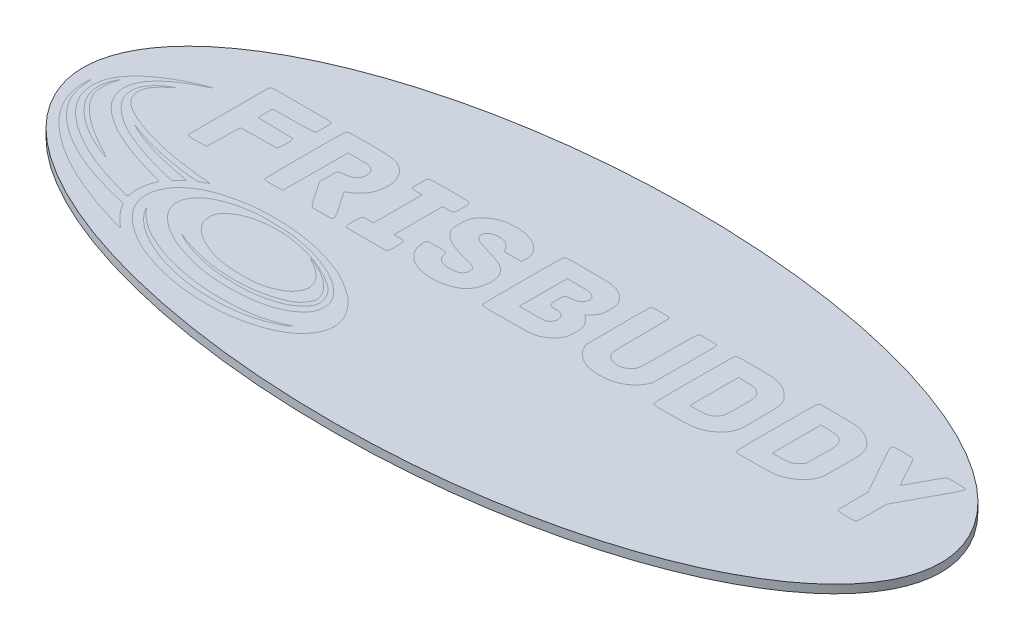
SolidWorks part; units mm, degrees
ref_plane "Front Plane" through (0, 0, 0) normal (0, 0, 1) x (1, 0, 0)
ref_plane "Top Plane" through (0, 0, 0) normal (0, 1, 0) x (1, 0, 0)
ref_plane "Right Plane" through (0, 0, 0) normal (1, 0, 0) x (0, 0, -1)
sketch "Sketch2" plane through (0, 0, 0) normal (0, 1, 0) x (1, 0, 0)
  line L0 (12795.8668, 8331.2) -> (12839.7, 8242.3)
  line L1 (12839.7, 8242.3) -> (13157.2, 8242.3)
  line L2 (13157.2, 8242.3) -> (13474.7, 8242.3)
  line L3 (13474.7, 8242.3) -> (13482.416, 8391.6503)
  line L4 (3889.7714, 6152.3459) -> (4203.7, 6159.5)
  line L5 (4203.7, 6159.5) -> (4216.4, 6756.4)
  line L6 (4216.4, 6756.4) -> (4229.1, 7353.3)
  line L7 (4229.1, 7353.3) -> (4875.6765, 7366)
  line L8 (4875.6765, 7366) -> (5522.2529, 7378.7)
  line L9 (5522.2529, 7378.7) -> (5539.8946, 7442.2)
  line L10 (5539.8946, 7899.4) -> (5522.2529, 7962.9)
  line L11 (5522.2529, 7962.9) -> (4875.6765, 7975.6)
  line L12 (4875.6765, 7975.6) -> (4229.1, 7988.3)
  line L13 (4229.1, 7988.3) -> (4229.1, 8255)
  line L14 (4229.1, 8255) -> (4229.1, 8521.7)
  line L15 (4229.1, 8521.7) -> (4950.8827, 8528.4527)
  line L16 (6629.6666, 6152.3194) -> (6946.9, 6159.5)
  line L17 (6946.9, 6159.5) -> (6953.5037, 7334.25)
  line L18 (6953.5037, 7334.25) -> (6960.1073, 8509)
  line L19 (6960.1073, 8509) -> (7330.665, 8509)
  line L20 (7340.989, 7391.2866) -> (7340.6, 7099.0732)
  line L21 (7340.6, 7099.0732) -> (7632.395, 6661.822)
  line L22 (8385.0518, 6152.3898) -> (8724.9, 6159.5)
  line L23 (8724.9, 6159.5) -> (8732.3803, 6223.5798)
  line L24 (9428.48, 8534.4) -> (9601.2, 8534.4)
  line L25 (9601.2, 8534.4) -> (9601.2, 7658.1)
  line L26 (9601.2, 7658.1) -> (9601.2, 6781.8)
  line L27 (9601.2, 6781.8) -> (9447.1302, 6781.8)
  line L28 (10491.8698, 6781.8) -> (10337.8, 6781.8)
  line L29 (10337.8, 6781.8) -> (10337.8, 7658.1)
  line L30 (10337.8, 7658.1) -> (10337.8, 8534.4)
  line L31 (10337.8, 8534.4) -> (10514.7063, 8534.4)
  line L32 (16368.6305, 7646.4318) -> (16277.3474, 7702.8479)
  line L33 (16277.3474, 7702.8479) -> (16378.2117, 7807.4739)
  line L34 (15284.45, 6807.2949) -> (14833.6, 6807.2)
  line L35 (14833.6, 6807.2) -> (14833.6, 7670.8)
  line L36 (14833.6, 7670.8) -> (14833.6, 8534.4)
  line L37 (14833.6, 8534.4) -> (15195.55, 8533.2938)
  line L38 (17226.5647, 7946.4102) -> (17233.9, 6794.5)
  line L39 (17233.9, 6794.5) -> (17301.5476, 6666.3406)
  line L40 (19554.185, 6666.997) -> (19621.5, 6794.5)
  line L41 (19621.5, 6794.5) -> (19628.8353, 7946.4102)
  line L42 (21253.45, 6781.9417) -> (21005.8, 6781.8)
  line L43 (21005.8, 6781.8) -> (21005.8, 7660.7753)
  line L44 (21005.8, 7660.7753) -> (21005.8, 8539.7506)
  line L45 (21005.8, 8539.7506) -> (21304.25, 8530.4365)
  line L46 (24912.9342, 7600.9946) -> (24904.7, 7065.7851)
  line L47 (24904.7, 7065.7851) -> (24826.4186, 6968.2425)
  line L48 (24237.95, 6782.9118) -> (23977.6, 6781.8)
  line L49 (23977.6, 6781.8) -> (23977.6, 7658.1)
  line L50 (23977.6, 7658.1) -> (23977.6, 8534.4)
  line L51 (23977.6, 8534.4) -> (24225.25, 8534.2583)
  line L52 (26450.8636, 8129.3236) -> (26924, 7279.7471)
  line L53 (26924, 7279.7471) -> (26924, 6743.7536)
  line L54 (27635.2, 6711.4393) -> (27635.2, 7245.2436)
  line L55 (27635.2, 7245.2436) -> (27892.9937, 7731.0718)
  line L56 (4367.5447, 4000.536) -> (4389.3162, 4061.6653)
  line L57 (4409.7294, 4119.3349) -> (4426.8469, 4167.9978)
  line L58 (4175.8386, 4581.3338) -> (4630.5773, 4467.116)
  line L59 (4630.5773, 4467.116) -> (4766.2229, 4601.0766)
  line L60 (4766.2229, 4601.0766) -> (4901.8685, 4735.0373)
  line L61 (4901.8685, 4735.0373) -> (4438.4842, 4827.4746)
  line L62 (4740.6589, 4938.348) -> (5125.2179, 4893.0496)
  line L63 (5125.2179, 4893.0496) -> (5267.6486, 4967.4748)
  line L64 (4575.7237, 2721.8023) -> (4471.4646, 2883.0161)
  line L65 (4471.4646, 2883.0161) -> (4020.0823, 2993.4518)
  line L66 (52.7635, 5956.3) -> (36.2974, 6184.9)
  line L67 (36.2974, 6184.9) -> (16.0218, 6005.2411)
  line L68 (10275.9668, 4676.2564) -> (10212.1371, 4700.1686)
  arc A0 (11932.2256, 9180.7034) -> (11721.9671, 9109.6363) centre (12229.2792, 7955.2754) ccw
  arc A1 (11721.9671, 9109.6363) -> (11533.1914, 9004.2135) centre (12179.3289, 8068.9325) ccw
  arc A2 (11533.1914, 9004.2135) -> (11375.4395, 8870.1976) centre (12124.4034, 8148.436) ccw
  arc A3 (11375.4395, 8870.1976) -> (11257.1444, 8714.3245) centre (11975.2816, 8292.1412) ccw
  arc A4 (11257.1444, 8714.3245) -> (11218.7801, 8638.5564) centre (11840.8094, 8371.1959) ccw
  arc A5 (11218.7801, 8638.5564) -> (11199.2516, 8572.7753) centre (11487.9788, 8522.8497) ccw
  arc A6 (11199.2516, 8572.7753) -> (11190.7465, 8486.1073) centre (11784.2952, 8471.6112) ccw
  arc A7 (11190.7465, 8486.1073) -> (11188.7, 8318.5) centre (18052.9947, 8318.5034) ccw
  arc A8 (11188.7, 8318.5) -> (11190.8486, 8169.6032) centre (16348.7852, 8318.4954) ccw
  arc A9 (11190.8486, 8169.6032) -> (11198.467, 8074.1573) centre (12133.4062, 8196.8104) ccw
  arc A10 (11198.467, 8074.1573) -> (11213.3947, 8003.0575) centre (11669.6997, 8135.9776) ccw
  arc A11 (11213.3947, 8003.0575) -> (11238.5394, 7938.5915) centre (11589.4604, 8112.6039) ccw
  arc A12 (11238.5394, 7938.5915) -> (11370.7083, 7760.9469) centre (11794.6485, 8214.3513) ccw
  arc A13 (11370.7083, 7760.9469) -> (11578.8412, 7606.4499) centre (12153.825, 8598.4903) ccw
  arc A14 (11578.8412, 7606.4499) -> (11866.8623, 7472.3074) centre (12470.9347, 9145.6091) ccw
  arc A15 (11866.8623, 7472.3074) -> (12242.8, 7356.5239) centre (13268.1097, 11353.8131) ccw
  arc A16 (12495.8303, 7289.836) -> (12242.8, 7356.5239) centre (7324.8937, -11816.5716) ccw
  arc A17 (12634.887, 7247.1205) -> (12495.8303, 7289.836) centre (11932.3036, 5207.6208) ccw
  arc A18 (12722.2451, 7210.9021) -> (12634.887, 7247.1205) centre (12383.3667, 6516.9958) ccw
  arc A19 (12781.0638, 7171.0983) -> (12722.2451, 7210.9021) centre (12611.0728, 6983.2603) ccw
  arc A20 (12834.9768, 7078.9858) -> (12781.0638, 7171.0983) centre (12662.0831, 7039.6257) ccw
  arc A21 (12834.6741, 6960.0906) -> (12834.9768, 7078.9858) centre (12576.733, 7020.1953) ccw
  arc A22 (12781.2574, 6846.75) -> (12834.6741, 6960.0906) centre (12544.0131, 7027.8194) ccw
  arc A23 (12687.8486, 6771.0627) -> (12781.2574, 6846.75) centre (12578.4995, 7001.4986) ccw
  arc A24 (12578.8426, 6740.2257) -> (12687.8486, 6771.0627) centre (12542.0884, 7078.2295) ccw
  arc A25 (12410.0714, 6730.9847) -> (12578.8426, 6740.2257) centre (12408.3573, 8308.0689) ccw
  arc A26 (12239.386, 6740.0911) -> (12410.0714, 6730.9847) centre (12408.363, 8303.119) ccw
  arc A27 (12121.3342, 6770.4474) -> (12239.386, 6740.0911) centre (12285.0338, 7162.3324) ccw
  arc A28 (12026.2927, 6821.2519) -> (12121.3342, 6770.4474) centre (12339.8034, 7293.4453) ccw
  arc A29 (11950.3246, 6885.9743) -> (12026.2927, 6821.2519) centre (12257.779, 7169.9045) ccw
  arc A30 (11897.4789, 6960.9279) -> (11950.3246, 6885.9743) centre (12207.1689, 7123.1675) ccw
  arc A31 (11870.5632, 7041.9949) -> (11897.4789, 6960.9279) centre (12132.034, 7083.806) ccw
  arc A32 (11870.5632, 7041.9949) -> (11861.1744, 7081.9384) centre (11590.1101, 6997.149) ccw
  arc A33 (11861.1744, 7081.9384) -> (11846.3873, 7118.4516) centre (11630.6347, 7009.825) ccw
  arc A34 (11846.3873, 7118.4516) -> (11828.3733, 7147.3902) centre (11677.6982, 7033.5205) ccw
  arc A35 (11828.3733, 7147.3902) -> (11809.2759, 7163.7227) centre (11781.6293, 7112.0644) ccw
  arc A36 (11809.2759, 7163.7227) -> (11733.6936, 7183.7124) centre (11729.3376, 7014.3561) ccw
  arc A37 (11733.6936, 7183.7124) -> (11477.8289, 7187.2485) centre (11457.1404, -3568.3723) ccw
  arc A38 (11477.8289, 7187.2485) -> (11219.7916, 7184.9812) centre (11454.6536, -4860.098) ccw
  arc A39 (11219.7916, 7184.9812) -> (11153.2659, 7164.9851) centre (11222.3076, 7055.9492) ccw
  arc A40 (11153.2659, 7164.9851) -> (11124.1021, 7112.5005) centre (11186.8187, 7111.9961) ccw
  arc A41 (11124.1021, 7112.5005) -> (11130.9843, 6970.5765) centre (12382.2385, 7102.3814) ccw
  arc A42 (11130.9843, 6970.5765) -> (11157.9238, 6815.3298) centre (12303.6185, 7094.0995) ccw
  arc A43 (11157.9238, 6815.3298) -> (11203.4912, 6688.182) centre (11781.4095, 6967.0364) ccw
  arc A44 (11203.4912, 6688.182) -> (11274.0708, 6573.8068) centre (11790.2669, 6971.3102) ccw
  arc A45 (11274.0708, 6573.8068) -> (11377.5791, 6456.2479) centre (12219.1149, 7301.5514) ccw
  arc A46 (11377.5791, 6456.2479) -> (11499.681, 6349.3691) centre (12270.526, 7353.1939) ccw
  arc A47 (11499.681, 6349.3691) -> (11626.6649, 6266.895) centre (12085.0622, 7111.6754) ccw
  arc A48 (11626.6649, 6266.895) -> (11883.5624, 6164.0628) centre (12194.7962, 7313.9033) ccw
  arc A49 (11883.5624, 6164.0628) -> (12191.3058, 6106.9575) centre (12389.7417, 8034.1147) ccw
  arc A50 (12191.3058, 6106.9575) -> (12512.0218, 6099.4948) centre (12398.5935, 8120.0726) ccw
  arc A51 (12512.0218, 6099.4948) -> (12808.1815, 6145.2351) centre (12425.4454, 7641.7194) ccw
  arc A52 (12808.1815, 6145.2351) -> (13134.7976, 6267.4237) centre (12405.871, 7718.2559) ccw
  arc A53 (13134.7976, 6267.4237) -> (13363.0747, 6442.3614) centre (12789.9099, 6953.8782) ccw
  arc A54 (13363.0747, 6442.3614) -> (13501.0643, 6679.5775) centre (12852.2207, 6898.27) ccw
  arc A55 (13501.0643, 6679.5775) -> (13558.9557, 6986.4921) centre (12430.3909, 7040.4489) ccw
  arc A56 (13558.9557, 6986.4921) -> (13556.8674, 7173.4517) centre (11973.8109, 7062.2779) ccw
  arc A57 (13556.8674, 7173.4517) -> (13529.9513, 7323.6065) centre (12846.1322, 7123.5386) ccw
  arc A58 (13529.9513, 7323.6065) -> (13474.6497, 7452.6177) centre (12968.8384, 7159.4395) ccw
  arc A59 (13474.6497, 7452.6177) -> (13386.8759, 7574.6492) centre (12811.7047, 7068.3626) ccw
  arc A60 (13386.8759, 7574.6492) -> (13271.6325, 7676.9438) centre (12915.7476, 7159.9463) ccw
  arc A61 (13271.6325, 7676.9438) -> (13116.8652, 7766.2485) centre (12633.9236, 6750.5392) ccw
  arc A62 (13116.8652, 7766.2485) -> (12903.8867, 7852.759) centre (12265.4289, 5975.5329) ccw
  arc A63 (12903.8867, 7852.759) -> (12602.5773, 7947.5612) centre (10693.3039, 1353.0998) ccw
  arc A64 (12248.4494, 8058.9545) -> (12602.5773, 7947.5612) centre (14853.3318, 15721.4827) ccw
  arc A65 (12052.2135, 8149.3506) -> (12248.4494, 8058.9545) centre (12583.4434, 9044.3711) ccw
  arc A66 (11949.4096, 8243.2924) -> (12052.2135, 8149.3506) centre (12227.0279, 8443.8782) ccw
  arc A67 (11912.6, 8357.0909) -> (11949.4096, 8243.2924) centre (12106.9112, 8357.0909) ccw
  arc A68 (11922.557, 8427.6093) -> (11912.6, 8357.0909) centre (12167.2951, 8357.0907) ccw
  arc A69 (11951.7653, 8481.6903) -> (11922.557, 8427.6093) centre (12061.1905, 8387.6635) ccw
  arc A70 (12006.5197, 8526.9619) -> (11951.7653, 8481.6903) centre (12110.9595, 8344.8981) ccw
  arc A71 (12096.8638, 8571.5313) -> (12006.5197, 8526.9619) centre (12407.6817, 7827.6395) ccw
  arc A72 (12295.7342, 8613.8445) -> (12096.8638, 8571.5313) centre (12308.645, 8064.6665) ccw
  arc A73 (12500.0401, 8582.1665) -> (12295.7342, 8613.8445) centre (12309.5067, 8028.0013) ccw
  arc A74 (12676.4908, 8482.7858) -> (12500.0401, 8582.1665) centre (12317.9252, 8052.4864) ccw
  arc A75 (12795.8668, 8331.2) -> (12676.4908, 8482.7858) centre (12378.8289, 8125.5746) ccw
  arc A76 (13482.416, 8391.6503) -> (13434.3245, 8649.7772) centre (12921.2452, 8420.6422) ccw
  arc A77 (13434.3245, 8649.7772) -> (13271.8625, 8884.0354) centre (12731.8385, 8336.0554) ccw
  arc A78 (13271.8625, 8884.0354) -> (13010.856, 9069.0115) centre (12573.8222, 8175.7126) ccw
  arc A79 (13010.856, 9069.0115) -> (12679.0112, 9183.3912) centre (12382.6049, 7784.8678) ccw
  arc A80 (12679.0112, 9183.3912) -> (12504.5666, 9208.5732) centre (12399.8018, 7866.0168) ccw
  arc A81 (12504.5666, 9208.5732) -> (12297.8811, 9216.2528) centre (12307.021, 6677.0742) ccw
  arc A82 (12297.8811, 9216.2528) -> (12094.7584, 9207.2044) centre (12306.824, 6731.0603) ccw
  arc A83 (12094.7584, 9207.2044) -> (11932.2256, 9180.7034) centre (12187.0622, 8129.4344) ccw
  arc A84 (3535.68, 9138.92) -> (3500.8028, 9054.7338) centre (3619.8811, 9054.7189) ccw
  arc A85 (3500.8028, 9054.7338) -> (3501.8596, 7653.6807) centre (801367.3805, 8956.0251) ccw
  arc A86 (3501.8596, 7653.6807) -> (3505.2921, 6249.2091) centre (870461.2352, 9070.3063) ccw
  arc A87 (3505.2921, 6249.2091) -> (3540.5214, 6174.506) centre (3602.7829, 6249.5264) ccw
  arc A88 (3540.5214, 6174.506) -> (3570.5642, 6161.4449) centre (3578.0312, 6219.7025) ccw
  arc A89 (3570.5642, 6161.4449) -> (3645.3368, 6154.2882) centre (3719.5422, 7323.7742) ccw
  arc A90 (3645.3368, 6154.2882) -> (3748.885, 6150.8938) centre (3752.5616, 7844.1599) ccw
  arc A91 (3748.885, 6150.8938) -> (3889.7714, 6152.3459) centre (3761.1454, 11796.7924) ccw
  arc A92 (5539.8946, 7442.2) -> (5553.407, 7525.8321) centre (5170.8036, 7544.7413) ccw
  arc A93 (5553.407, 7525.8321) -> (5556.9871, 7670.8) centre (2620.1217, 7670.8008) ccw
  arc A94 (5556.9871, 7670.8) -> (5553.407, 7815.7679) centre (2620.1217, 7670.7992) ccw
  arc A95 (5553.407, 7815.7679) -> (5539.8946, 7899.4) centre (5170.8036, 7796.8587) ccw
  arc A96 (4950.8827, 8528.4527) -> (5271.8207, 8533.0614) centre (4650.8527, 40598.6959) ccw
  arc A97 (5271.8207, 8533.0614) -> (5500.5129, 8540.5495) centre (5106.1038, 17090.1413) ccw
  arc A98 (5500.5129, 8540.5495) -> (5672.4238, 8549.8041) centre (4984.1216, 19734.216) ccw
  arc A99 (5672.4238, 8549.8041) -> (5706.5327, 8563.3128) centre (5668.7942, 8608.785) ccw
  arc A100 (5706.5327, 8563.3128) -> (5735.9008, 8622.2859) centre (5654.4785, 8626.0344) ccw
  arc A101 (5735.9008, 8622.2859) -> (5741.7695, 8848.4292) centre (103.2907, 8881.6068) ccw
  arc A102 (5741.7695, 8848.4292) -> (5738.3231, 9073.7371) centre (421.7599, 8879.7337) ccw
  arc A103 (5738.3231, 9073.7371) -> (5709.92, 9138.92) centre (5641.1928, 9070.1928) ccw
  arc A104 (5709.92, 9138.92) -> (5634.2061, 9170.4027) centre (5633.913, 9062.9131) ccw
  arc A105 (5634.2061, 9170.4027) -> (4622.8, 9171.7814) centre (4623.1196, -361578.7647) ccw
  arc A106 (4622.8, 9171.7814) -> (3611.3939, 9170.4027) centre (4622.4804, -361578.7647) ccw
  arc A107 (3611.3939, 9170.4027) -> (3535.68, 9138.92) centre (3611.687, 9062.9131) ccw
  arc A108 (6288.3143, 9129.4857) -> (6264.2599, 9075.7384) centre (6346.7017, 9071.0982) ccw
  arc A109 (6264.2599, 9075.7384) -> (6255.1049, 8856.3259) centre (13812.7306, 8650.8808) ccw
  arc A110 (6255.1049, 8856.3259) -> (6249.5686, 8487.3372) centre (21406.5619, 8444.4605) ccw
  arc A111 (6249.5686, 8487.3372) -> (6248.4, 7661.1404) centre (298397.6174, 7661.004) ccw
  arc A112 (6248.4, 7661.1404) -> (6249.778, 6937.4278) centre (196299.4875, 7661.1537) ccw
  arc A113 (6249.778, 6937.4278) -> (6255.087, 6521.9059) centre (29418.8895, 7025.6567) ccw
  arc A114 (6255.087, 6521.9059) -> (6262.8509, 6239.82) centre (30694.4807, 7053.4051) ccw
  arc A115 (6262.8509, 6239.82) -> (6280.4166, 6188.9241) centre (6354.1803, 6242.8614) ccw
  arc A116 (6280.4166, 6188.9241) -> (6311.0859, 6165.804) centre (6334.0056, 6228.1093) ccw
  arc A117 (6311.0859, 6165.804) -> (6361.9253, 6153.9826) centre (6383.9144, 6363.7816) ccw
  arc A118 (6361.9253, 6153.9826) -> (6449.7853, 6149.6844) centre (6444.5063, 6941.8996) ccw
  arc A119 (6449.7853, 6149.6844) -> (6629.6666, 6152.3194) centre (6374.7113, 17415.9355) ccw
  arc A120 (7520.8266, 8507.1254) -> (7330.665, 8509) centre (7330.6694, -1136.741) ccw
  arc A121 (7642.4303, 8500.4545) -> (7520.8266, 8507.1254) centre (7486.6082, 6771.6814) ccw
  arc A122 (7726.7411, 8488.1827) -> (7642.4303, 8500.4545) centre (7572.4185, 7723.6934) ccw
  arc A123 (7788.1116, 8467.7685) -> (7726.7411, 8488.1827) centre (7674.136, 8227.5836) ccw
  arc A124 (7900.331, 8385.609) -> (7788.1116, 8467.7685) centre (7629.3484, 8133.1997) ccw
  arc A125 (7972.363, 8268.9362) -> (7900.331, 8385.609) centre (7643.793, 8146.6541) ccw
  arc A126 (7993.9476, 8133.993) -> (7972.363, 8268.9362) centre (7646.2846, 8147.581) ccw
  arc A127 (7962.3118, 7999.6956) -> (7993.9476, 8133.993) centre (7633.2304, 8148.0907) ccw
  arc A128 (7903.8984, 7909.5199) -> (7962.3118, 7999.6956) centre (7637.1322, 8146.331) ccw
  arc A129 (7822.543, 7843.4171) -> (7903.8984, 7909.5199) centre (7661.6026, 8124.608) ccw
  arc A130 (7711.7141, 7798.5738) -> (7822.543, 7843.4171) centre (7602.5006, 8227.8687) ccw
  arc A131 (7564.2351, 7771.855) -> (7711.7141, 7798.5738) centre (7447.1412, 8838.5527) ccw
  arc A132 (7564.2351, 7771.855) -> (7491.5062, 7761.6445) centre (7697.1721, 6560.8263) ccw
  arc A133 (7491.5062, 7761.6445) -> (7429.4516, 7748.0264) centre (7607.108, 7086.6767) ccw
  arc A134 (7429.4516, 7748.0264) -> (7381.6708, 7732.8199) centre (7571.8628, 7217.8841) ccw
  arc A135 (7381.6708, 7732.8199) -> (7363.135, 7717.8341) centre (7394.5612, 7697.9196) ccw
  arc A136 (7363.135, 7717.8341) -> (7354.4965, 7692.5372) centre (7411.4691, 7687.2052) ccw
  arc A137 (7354.4965, 7692.5372) -> (7347.6548, 7607.748) centre (10662.5022, 7382.9426) ccw
  arc A138 (7347.6548, 7607.748) -> (7342.7209, 7505.7282) centre (9975.4012, 7429.5346) ccw
  arc A139 (7342.7209, 7505.7282) -> (7340.989, 7391.2866) centre (11487.4898, 7385.7686) ccw
  arc A140 (7632.395, 6661.822) -> (7748.5786, 6491.4362) centre (16212.9726, 12387.9866) ccw
  arc A141 (7748.5786, 6491.4362) -> (7856.2492, 6341.3674) centre (13201.8649, 10290.371) ccw
  arc A142 (7856.2492, 6341.3674) -> (7949.2022, 6217.8793) centre (14770.6678, 11449.3216) ccw
  arc A143 (7949.2022, 6217.8793) -> (7984.6969, 6184.9252) centre (8063.9499, 6305.8806) ccw
  arc A144 (7984.6969, 6184.9252) -> (8031.3618, 6165.1097) centre (8062.9509, 6304.356) ccw
  arc A145 (8031.3618, 6165.1097) -> (8100.4313, 6154.5235) centre (8140.3255, 6645.4307) ccw
  arc A146 (8100.4313, 6154.5235) -> (8206.0777, 6150.3419) centre (8203.5757, 7423.752) ccw
  arc A147 (8206.0777, 6150.3419) -> (8385.0518, 6152.3898) centre (8187.5073, 15594.7001) ccw
  arc A148 (8732.3803, 6223.5798) -> (8723.4606, 6273.6) centre (8644.9215, 6233.7892) ccw
  arc A149 (8723.4606, 6273.6) -> (8667.361, 6375.7011) centre (7161.7722, 5481.9921) ccw
  arc A150 (8667.361, 6375.7011) -> (8574.5962, 6522.6563) centre (5938.25, 4755.7186) ccw
  arc A151 (8574.5962, 6522.6563) -> (8421.2303, 6747.7591) centre (-6280.15, -3433.3117) ccw
  arc A152 (8299.0767, 6925.2326) -> (8421.2303, 6747.7591) centre (39321.9721, 28147.2648) ccw
  arc A153 (8196.1977, 7077.1266) -> (8299.0767, 6925.2326) centre (24672.0743, 18125.5895) ccw
  arc A154 (8105.9194, 7211.9732) -> (8196.1977, 7077.1266) centre (97335.3007, 66852.3482) ccw
  arc A155 (8102.6, 7222.913) -> (8105.9194, 7211.9732) centre (8122.2868, 7222.913) ccw
  arc A156 (8106.754, 7231.0018) -> (8102.6, 7222.913) centre (8112.5522, 7222.913) ccw
  arc A157 (8133.4799, 7249.299) -> (8106.754, 7231.0018) centre (8543.7332, 6621.3954) ccw
  arc A158 (8167.4379, 7269.955) -> (8133.4799, 7249.299) centre (8470.5231, 6733.4466) ccw
  arc A159 (8207.7231, 7291.5974) -> (8167.4379, 7269.955) centre (8696.9478, 6332.6394) ccw
  arc A160 (8207.7231, 7291.5974) -> (8323.6339, 7367.1455) centre (7910.2527, 7874.688) ccw
  arc A161 (8323.6339, 7367.1455) -> (8441.7044, 7477.2701) centre (7563.1395, 8300.87) ccw
  arc A162 (8441.7044, 7477.2701) -> (8546.6646, 7605.2054) centre (7527.1491, 8334.6092) ccw
  arc A163 (8546.6646, 7605.2054) -> (8623.2493, 7734.8539) centre (7845.5942, 8106.779) ccw
  arc A164 (8623.2493, 7734.8539) -> (8680.2837, 7898.8897) centre (7919.154, 8071.5976) ccw
  arc A165 (8680.2837, 7898.8897) -> (8709.0218, 8093.8077) centre (7427.3275, 8183.1991) ccw
  arc A166 (8709.0218, 8093.8077) -> (8707.7527, 8293.6266) centre (7396.0343, 8185.3818) ccw
  arc A167 (8707.7527, 8293.6266) -> (8674.7022, 8472.5878) centre (7801.983, 8218.8816) ccw
  arc A168 (8674.7022, 8472.5878) -> (8594.4486, 8669.3282) centre (7695.7673, 8188.0032) ccw
  arc A169 (8594.4486, 8669.3282) -> (8476.9087, 8839.255) centre (7789.8308, 8238.382) ccw
  arc A170 (8476.9087, 8839.255) -> (8325.8579, 8976.3914) centre (7808.1688, 8254.4189) ccw
  arc A171 (8325.8579, 8976.3914) -> (8146.6775, 9076.3655) centre (7796.3744, 8237.9714) ccw
  arc A172 (8146.6775, 9076.3655) -> (7992.3621, 9120.9165) centre (7876.1999, 8429.0203) ccw
  arc A173 (7992.3621, 9120.9165) -> (7768.0348, 9148.7776) centre (7554.6998, 6514.052) ccw
  arc A174 (7768.0348, 9148.7776) -> (7453.9658, 9164.708) centre (7346.5755, 3943.6052) ccw
  arc A175 (7453.9658, 9164.708) -> (6997.6764, 9169.4) centre (6997.6619, -13021.1111) ccw
  arc A176 (6997.6764, 9169.4) -> (6623.2318, 9168.08) centre (6997.6362, -43928.736) ccw
  arc A177 (6623.2318, 9168.08) -> (6440.3244, 9162.2928) centre (6649.4818, 5445.0943) ccw
  arc A178 (6440.3244, 9162.2928) -> (6332.8483, 9151.705) centre (6512.5936, 7877.9031) ccw
  arc A179 (6332.8483, 9151.705) -> (6288.3143, 9129.4857) centre (6343.8152, 9073.9849) ccw
  arc A180 (9225.28, 9138.92) -> (9198.2882, 9077.0878) centre (9290.6032, 9073.5967) ccw
  arc A181 (9198.2882, 9077.0878) -> (9194.0316, 8851.9) centre (15152.9768, 8851.8966) ccw
  arc A182 (9194.0316, 8851.9) -> (9198.2882, 8626.7122) centre (15152.9768, 8851.9034) ccw
  arc A183 (9198.2882, 8626.7122) -> (9225.28, 8564.88) centre (9290.6032, 8630.2033) ccw
  arc A184 (9225.28, 8564.88) -> (9247.2883, 8552.5146) centre (9258.3236, 8597.9236) ccw
  arc A185 (9247.2883, 8552.5146) -> (9295.8521, 8542.9912) centre (9377.8999, 9089.9726) ccw
  arc A186 (9295.8521, 8542.9912) -> (9357.5939, 8536.5229) centre (9399.3418, 9232.9227) ccw
  arc A187 (9357.5939, 8536.5229) -> (9428.48, 8534.4) centre (9428.4808, 9718.999) ccw
  arc A188 (9447.1302, 6781.8) -> (9291.3156, 6773.7727) centre (9447.1305, 5265.5561) ccw
  arc A189 (9291.3156, 6773.7727) -> (9228.6824, 6739.7289) centre (9300.836, 6681.6194) ccw
  arc A190 (9228.6824, 6739.7289) -> (9200.4558, 6666.4259) centre (9328.817, 6659.0844) ccw
  arc A191 (9200.4558, 6666.4259) -> (9194.8, 6468.4863) centre (12661.2786, 6468.4872) ccw
  arc A192 (9194.8, 6468.4863) -> (9196.6615, 6354.1122) centre (12709.5133, 6468.4868) ccw
  arc A193 (9196.6615, 6354.1122) -> (9202.6347, 6266.9433) centre (10414.1881, 6393.7537) ccw
  arc A194 (9202.6347, 6266.9433) -> (9211.7503, 6203.1158) centre (10056.2504, 6356.2891) ccw
  arc A195 (9211.7503, 6203.1158) -> (9225.28, 6177.28) centre (9259.8376, 6211.8377) ccw
  arc A196 (9225.28, 6177.28) -> (9298.6816, 6146.6246) centre (9299.2929, 6251.2928) ccw
  arc A197 (9298.6816, 6146.6246) -> (9969.5, 6144.6655) centre (9969.5614, 121011.5679) ccw
  arc A198 (9969.5, 6144.6655) -> (10640.3184, 6146.6246) centre (9969.4386, 121011.5679) ccw
  arc A199 (10640.3184, 6146.6246) -> (10713.72, 6177.28) centre (10639.7071, 6251.2928) ccw
  arc A200 (10713.72, 6177.28) -> (10727.2497, 6203.1158) centre (10679.1624, 6211.8377) ccw
  arc A201 (10727.2497, 6203.1158) -> (10736.3653, 6266.9433) centre (9882.7496, 6356.2891) ccw
  arc A202 (10736.3653, 6266.9433) -> (10742.3385, 6354.1122) centre (9524.8119, 6393.7537) ccw
  arc A203 (10742.3385, 6354.1122) -> (10744.2, 6468.4863) centre (7229.4867, 6468.4868) ccw
  arc A204 (10744.2, 6468.4863) -> (10738.5442, 6666.4259) centre (7277.7214, 6468.4872) ccw
  arc A205 (10738.5442, 6666.4259) -> (10710.3176, 6739.7289) centre (10610.183, 6659.0844) ccw
  arc A206 (10710.3176, 6739.7289) -> (10647.6844, 6773.7727) centre (10638.164, 6681.6194) ccw
  arc A207 (10647.6844, 6773.7727) -> (10491.8698, 6781.8) centre (10491.8695, 5265.5561) ccw
  arc A208 (10514.7063, 8534.4) -> (10651.5433, 8543.7714) centre (10514.7069, 9538.0981) ccw
  arc A209 (10651.5433, 8543.7714) -> (10711.4295, 8579.7373) centre (10639.4321, 8631.7781) ccw
  arc A210 (10711.4295, 8579.7373) -> (10738.5911, 8656.1377) centre (10594.2813, 8664.4138) ccw
  arc A211 (10738.5911, 8656.1377) -> (10744.2, 8851.9) centre (7325.1736, 8851.899) ccw
  arc A212 (10744.2, 8851.9) -> (10730.2473, 9065.7459) centre (9098.49, 8851.9014) ccw
  arc A213 (10730.2473, 9065.7459) -> (10673.1137, 9140.108) centre (10637.4613, 9053.5862) ccw
  arc A214 (10673.1137, 9140.108) -> (10544.1318, 9166.3567) centre (10540.4154, 8818.0733) ccw
  arc A215 (10544.1318, 9166.3567) -> (9973.6863, 9169.4) centre (9973.6397, -44304.3246) ccw
  arc A216 (9973.6863, 9169.4) -> (9629.1553, 9167.8989) centre (9973.7243, -30377.8813) ccw
  arc A217 (9629.1553, 9167.8989) -> (9411.1388, 9162.5108) centre (9688.5558, 2350.9213) ccw
  arc A218 (9411.1388, 9162.5108) -> (9259.6455, 9154.4847) centre (9663.6177, 2963.1913) ccw
  arc A219 (9259.6455, 9154.4847) -> (9225.28, 9138.92) centre (9263.1308, 9101.0692) ccw
  arc A220 (14123.2937, 9120.2698) -> (14110.7907, 9072.6989) centre (14216.6582, 9070.3025) ccw
  arc A221 (14110.7907, 9072.6989) -> (14103.6868, 8721.9399) centre (87734.126, 7406.1485) ccw
  arc A222 (14103.6868, 8721.9399) -> (14098.5517, 8272.4082) centre (48969.799, 8098.8639) ccw
  arc A223 (14098.5517, 8272.4082) -> (14097, 7648.8841) centre (139403.8675, 7648.8126) ccw
  arc A224 (14097, 7648.8841) -> (14098.1388, 6810.8761) centre (322642.356, 7649.167) ccw
  arc A225 (14098.1388, 6810.8761) -> (14103.7196, 6450.7738) centre (28188.8634, 6849.1596) ccw
  arc A226 (14103.7196, 6450.7738) -> (14113.2514, 6240.9461) centre (20236.1812, 6624.221) ccw
  arc A227 (14113.2514, 6240.9461) -> (14138.3968, 6185.2318) centre (14199.5107, 6246.3457) ccw
  arc A228 (14138.3968, 6185.2318) -> (14188.0738, 6161.432) centre (14197.0242, 6243.8591) ccw
  arc A229 (14188.0738, 6161.432) -> (14317.7252, 6152.1199) centre (14380.5463, 7933.9847) ccw
  arc A230 (14317.7252, 6152.1199) -> (14545.1855, 6148.7398) centre (14514.3656, 11729.7818) ccw
  arc A231 (14545.1855, 6148.7398) -> (15059.1468, 6152.7702) centre (13933.5421, 116918.1119) ccw
  arc A232 (15059.1468, 6152.7702) -> (15604.9446, 6159.6332) centre (13909.3687, 119298.1994) ccw
  arc A233 (15604.9446, 6159.6332) -> (15833.3104, 6168.5581) centre (15533.8059, 10906.0123) ccw
  arc A234 (15833.3104, 6168.5581) -> (15972.4309, 6185.5808) centre (15757.8348, 7362.3963) ccw
  arc A235 (15972.4309, 6185.5808) -> (16090.9, 6217.9989) centre (15845.2471, 6883.0405) ccw
  arc A236 (16090.9, 6217.9989) -> (16240.6593, 6286.9996) centre (15723.9011, 7211.5525) ccw
  arc A237 (16240.6593, 6286.9996) -> (16374.3449, 6377.0941) centre (15768.2288, 7132.2414) ccw
  arc A238 (16374.3449, 6377.0941) -> (16485.8792, 6483.8298) centre (15818.6956, 7069.3661) ccw
  arc A239 (16485.8792, 6483.8298) -> (16569.7426, 6602.3406) centre (15962.7132, 6942.9727) ccw
  arc A240 (16569.7426, 6602.3406) -> (16610.9855, 6684.7519) centre (15720.7635, 7078.7401) ccw
  arc A241 (16610.9855, 6684.7519) -> (16635.0732, 6755.4052) centre (16223.0338, 6856.4486) ccw
  arc A242 (16635.0732, 6755.4052) -> (16648.9548, 6837.5392) centre (16080.8647, 6891.313) ccw
  arc A243 (16648.9548, 6837.5392) -> (16657.7647, 6961.2812) centre (13998.54, 7088.4211) ccw
  arc A244 (16657.7647, 6961.2812) -> (16660.0477, 7059.9249) centre (14657.1867, 7056.9312) ccw
  arc A245 (16660.0477, 7059.9249) -> (16656.9712, 7149.4888) centre (15295.4858, 7057.8861) ccw
  arc A246 (16656.9712, 7149.4888) -> (16649.0698, 7225.3211) centre (15618.6516, 7079.6284) ccw
  arc A247 (16649.0698, 7225.3211) -> (16636.2912, 7280.4406) centre (16327.9682, 7179.92) ccw
  arc A248 (16636.2912, 7280.4406) -> (16590.9452, 7386.7336) centre (16011.7835, 7076.8364) ccw
  arc A249 (16590.9452, 7386.7336) -> (16524.5082, 7492.378) centre (15805.0611, 6966.2239) ccw
  arc A250 (16524.5082, 7492.378) -> (16447.0332, 7583.7346) centre (15851.6957, 7000.3287) ccw
  arc A251 (16447.0332, 7583.7346) -> (16368.6305, 7646.4318) centre (16149.9582, 7292.6129) ccw
  arc A252 (16378.2117, 7807.4739) -> (16480.6399, 7927.5728) centre (15445.2136, 8706.9247) ccw
  arc A253 (16480.6399, 7927.5728) -> (16536.7981, 8030.2738) centre (16156.6353, 8171.4468) ccw
  arc A254 (16536.7981, 8030.2738) -> (16564.1279, 8150.5067) centre (16097.8836, 8193.2647) ccw
  arc A255 (16564.1279, 8150.5067) -> (16572.6972, 8331.2) centre (14519.3369, 8338.0308) ccw
  arc A256 (16572.6972, 8331.2) -> (16570.722, 8470.7197) centre (12582.0906, 8344.4773) ccw
  arc A257 (16570.722, 8470.7197) -> (16561.911, 8553.6925) centre (16007.8791, 8452.9052) ccw
  arc A258 (16561.911, 8553.6925) -> (16542.339, 8621.6569) centre (16214.9286, 8490.5704) ccw
  arc A259 (16542.339, 8621.6569) -> (16505.2812, 8701.7865) centre (15759.1549, 8308.0898) ccw
  arc A260 (16505.2812, 8701.7865) -> (16395.5502, 8856.7563) centre (15860.5029, 8361.5655) ccw
  arc A261 (16395.5502, 8856.7563) -> (16245.1171, 8985.7896) centre (15762.2488, 8270.6317) ccw
  arc A262 (16245.1171, 8985.7896) -> (16060.7026, 9082.9837) centre (15708.1595, 8190.5248) ccw
  arc A263 (16060.7026, 9082.9837) -> (15850.6248, 9143.8056) centre (15634.4571, 8003.9529) ccw
  arc A264 (15850.6248, 9143.8056) -> (15762.087, 9153.8965) centre (15738.2419, 8551.2148) ccw
  arc A265 (15762.087, 9153.8965) -> (15525.2925, 9161.8817) centre (14959.5669, -11129.3351) ccw
  arc A266 (15525.2925, 9161.8817) -> (15242.3755, 9167.5318) centre (15026.5095, -8727.5644) ccw
  arc A267 (15242.3755, 9167.5318) -> (14932.6268, 9169.4) centre (14932.6413, -16506.755) ccw
  arc A268 (14932.6268, 9169.4) -> (14438.9194, 9168.3487) centre (14932.5642, -106724.7607) ccw
  arc A269 (14438.9194, 9168.3487) -> (14256.8167, 9162.4384) centre (14452.6844, 5935.8892) ccw
  arc A270 (14256.8167, 9162.4384) -> (14162.2343, 9149.5534) centre (14295.5325, 8524.6623) ccw
  arc A271 (14162.2343, 9149.5534) -> (14123.2937, 9120.2698) centre (14174.3045, 9092.9696) ccw
  arc A272 (15795.0602, 8460.4288) -> (15671.06, 8510.2785) centre (15604.6045, 8165.8229) ccw
  arc A273 (15875.2084, 8371.645) -> (15795.0602, 8460.4288) centre (15669.9765, 8266.9433) ccw
  arc A274 (15898.9253, 8256.3549) -> (15875.2084, 8371.645) centre (15677.853, 8270.9616) ccw
  arc A275 (15864.2049, 8131.6836) -> (15898.9253, 8256.3549) centre (15582.7147, 8277.2477) ccw
  arc A276 (15818.4035, 8072.5777) -> (15864.2049, 8131.6836) centre (15680.722, 8226.5663) ccw
  arc A277 (15751.9637, 8029.4619) -> (15818.4035, 8072.5777) centre (15646.2263, 8265.1476) ccw
  arc A278 (15659.0657, 8000.173) -> (15751.9637, 8029.4619) centre (15580.1685, 8412.3884) ccw
  arc A279 (15532.1, 7982.6891) -> (15659.0657, 8000.173) centre (15428.4771, 9204.9338) ccw
  arc A280 (15532.1, 7982.6891) -> (15465.974, 7974.6644) centre (15609.8707, 7065.3809) ccw
  arc A281 (15465.974, 7974.6644) -> (15411.6159, 7962.5949) centre (15536.7324, 7527.5428) ccw
  arc A282 (15411.6159, 7962.5949) -> (15370.6412, 7947.4745) centre (15493.8244, 7676.7404) ccw
  arc A283 (15370.6412, 7947.4745) -> (15347.95, 7929.7296) centre (15396.0808, 7891.5629) ccw
  arc A284 (15347.95, 7929.7296) -> (15319.3136, 7855.061) centre (15452.5397, 7846.7925) ccw
  arc A285 (15319.3136, 7855.061) -> (15315.2352, 7680.1582) centre (17577.6741, 7714.9017) ccw
  arc A286 (15315.2352, 7680.1582) -> (15325.0801, 7505.3884) centre (17454.6655, 7713.0117) ccw
  arc A287 (15325.0801, 7505.3884) -> (15355.7403, 7422.4517) centre (15498.2531, 7522.2716) ccw
  arc A288 (15355.7403, 7422.4517) -> (15383.3445, 7393.2144) centre (15469.1903, 7501.9151) ccw
  arc A289 (15383.3445, 7393.2144) -> (15415.8901, 7376.3661) centre (15443.2404, 7469.0566) ccw
  arc A290 (15415.8901, 7376.3661) -> (15463.773, 7368.1704) centre (15474.5733, 7575.2452) ccw
  arc A291 (15463.773, 7368.1704) -> (15547.0561, 7366) centre (15547.0568, 8964.9707) ccw
  arc A292 (15683.4608, 7356.4619) -> (15547.0561, 7366) centre (15547.0565, 6385.8703) ccw
  arc A293 (15787.7717, 7326.8001) -> (15683.4608, 7356.4619) centre (15628.3766, 6964.5049) ccw
  arc A294 (15864.2693, 7275.9349) -> (15787.7717, 7326.8001) centre (15679.8985, 7081.6104) ccw
  arc A295 (15917.1257, 7203.1849) -> (15864.2693, 7275.9349) centre (15694.5376, 7097.04) ccw
  arc A296 (15942.3543, 7108.4943) -> (15917.1257, 7203.1849) centre (15676.1682, 7088.28) ccw
  arc A297 (15932.125, 7010.0504) -> (15942.3543, 7108.4943) centre (15665.7172, 7087.4862) ccw
  arc A298 (15888.1126, 6921.9477) -> (15932.125, 7010.0504) centre (15668.6152, 7086.6441) ccw
  arc A299 (15816.4665, 6856.8802) -> (15888.1126, 6921.9477) centre (15682.9116, 7075.9171) ccw
  arc A300 (15753.7961, 6829.9515) -> (15816.4665, 6856.8802) centre (15690.7576, 7063.0488) ccw
  arc A301 (15674.0893, 6815.5686) -> (15753.7961, 6829.9515) centre (15630.1294, 7287.2336) ccw
  arc A302 (15546.3543, 6808.8715) -> (15674.0893, 6815.5686) centre (15527.6942, 8386.2936) ccw
  arc A303 (15284.45, 6807.2949) -> (15546.3543, 6808.8715) centre (15279.6786, 29354.7467) ccw
  arc A304 (15342.4502, 8531.2624) -> (15195.55, 8533.2938) centre (15174.7137, 1713.8646) ccw
  arc A305 (15484.5355, 8526.0768) -> (15342.4502, 8531.2624) centre (15195.2843, 2549.8666) ccw
  arc A306 (15605.7033, 8518.862) -> (15484.5355, 8526.0768) centre (15220.4324, 3069.5377) ccw
  arc A307 (15671.06, 8510.2785) -> (15605.7033, 8518.862) centre (15566.941, 7970.6028) ccw
  arc A308 (17248.7248, 9133.8602) -> (17233.4209, 9093.3467) centre (17299.9152, 9091.3759) ccw
  arc A309 (17233.4209, 9093.3467) -> (17227.4924, 8847.8624) centre (39603.9982, 8430.2753) ccw
  arc A310 (17227.4924, 8847.8624) -> (17224.4682, 8501.8266) centre (34666.8722, 8522.4214) ccw
  arc A311 (17224.4682, 8501.8266) -> (17226.5647, 7946.4102) centre (124283.2324, 8628.2215) ccw
  arc A312 (17301.5476, 6666.3406) -> (17483.7547, 6425.4099) centre (18130.5459, 7103.9179) ccw
  arc A313 (17483.7547, 6425.4099) -> (17738.9695, 6245.1799) centre (18221.6398, 7199.4792) ccw
  arc A314 (17738.9695, 6245.1799) -> (18058.0686, 6134.1276) centre (18312.4232, 7378.971) ccw
  arc A315 (18058.0686, 6134.1276) -> (18427.7, 6096.7509) centre (18427.6994, 7943.1411) ccw
  arc A316 (18427.7, 6096.7509) -> (18794.9737, 6134.5724) centre (18427.701, 7898.8971) ccw
  arc A317 (18794.9737, 6134.5724) -> (19115.2025, 6246.7412) centre (18531.6621, 7399.4878) ccw
  arc A318 (19115.2025, 6246.7412) -> (19372.2226, 6427.4844) centre (18621.6987, 7221.6278) ccw
  arc A319 (19372.2226, 6427.4844) -> (19554.185, 6666.997) centre (18739.2616, 7097.2337) ccw
  arc A320 (19628.8353, 7946.4102) -> (19630.9318, 8501.8266) centre (-87427.8324, 8628.2215) ccw
  arc A321 (19630.9318, 8501.8266) -> (19627.9076, 8847.8624) centre (2188.5278, 8522.4214) ccw
  arc A322 (19627.9076, 8847.8624) -> (19621.9791, 9093.3467) centre (-2748.5982, 8430.2753) ccw
  arc A323 (19621.9791, 9093.3467) -> (19606.6752, 9133.8602) centre (19555.4848, 9091.3759) ccw
  arc A324 (19606.6752, 9133.8602) -> (19544.069, 9164.8578) centre (19540.5104, 9078.9482) ccw
  arc A325 (19544.069, 9164.8578) -> (19282.8183, 9171.2786) centre (19222.656, 1405.3151) ccw
  arc A326 (19282.8183, 9171.2786) -> (19022.5713, 9168.67) centre (19226.0889, 1847.9025) ccw
  arc A327 (19022.5713, 9168.67) -> (18953.48, 9138.92) centre (19025.3977, 9067.0023) ccw
  arc A328 (18953.48, 9138.92) -> (18937.4375, 9102.5169) centre (18992.3429, 9100.0571) ccw
  arc A329 (18937.4375, 9102.5169) -> (18929.7414, 8896.4558) centre (32781.5939, 8482.2826) ccw
  arc A330 (18929.7414, 8896.4558) -> (18924.4433, 8601.1931) centre (31280.7373, 8527.1531) ccw
  arc A331 (18924.4433, 8601.1931) -> (18923, 8119.5169) centre (99310.0946, 8119.4837) ccw
  arc A332 (18921.3385, 7673.1762) -> (18923, 8119.5169) centre (-41037.4111, 8119.5478) ccw
  arc A333 (18915.8433, 7351.0751) -> (18921.3385, 7673.1762) centre (2167.3041, 7797.9087) ccw
  arc A334 (18907.6073, 7114.4235) -> (18915.8433, 7351.0751) centre (4332.6439, 7740.1369) ccw
  arc A335 (18894.0379, 7033.9271) -> (18907.6073, 7114.4235) centre (18578.1591, 7128.5669) ccw
  arc A336 (18721.6174, 6812.1631) -> (18894.0379, 7033.9271) centre (18521.7536, 7145.4664) ccw
  arc A337 (18420.064, 6731.4277) -> (18721.6174, 6812.1631) centre (18429.6943, 7298.989) ccw
  arc A338 (18122.5198, 6822.4592) -> (18420.064, 6731.4277) centre (18429.6171, 7294.4434) ccw
  arc A339 (17960.1292, 7049.7727) -> (18122.5198, 6822.4592) centre (18331.2204, 7143.2147) ccw
  arc A340 (17947.7614, 7135.6817) -> (17960.1292, 7049.7727) centre (18366.7062, 7152.1499) ccw
  arc A341 (17939.6485, 7385.7862) -> (17947.7614, 7135.6817) centre (36167.3685, 7851.8748) ccw
  arc A342 (17934.13, 7712.5584) -> (17939.6485, 7385.7862) centre (36759.8163, 7867.0496) ccw
  arc A343 (17932.4, 8134.1676) -> (17934.13, 7712.5584) centre (69298.7, 8134.1345) ccw
  arc A344 (17932.4, 8134.1676) -> (17930.9544, 8608.4254) centre (-59866.3379, 8134.1554) ccw
  arc A345 (17930.9544, 8608.4254) -> (17925.6527, 8899.5139) centre (5916.1796, 8535.1889) ccw
  arc A346 (17925.6527, 8899.5139) -> (17917.9419, 9102.6029) centre (4599.4392, 8495.2435) ccw
  arc A347 (17917.9419, 9102.6029) -> (17901.92, 9138.92) centre (17863.102, 9100.102) ccw
  arc A348 (17901.92, 9138.92) -> (17832.8287, 9168.67) centre (17830.0023, 9067.0023) ccw
  arc A349 (17832.8287, 9168.67) -> (17572.5817, 9171.2786) centre (17629.3111, 1847.9025) ccw
  arc A350 (17572.5817, 9171.2786) -> (17311.331, 9164.8578) centre (17632.744, 1405.3151) ccw
  arc A351 (17311.331, 9164.8578) -> (17248.7248, 9133.8602) centre (17314.8896, 9078.9482) ccw
  arc A352 (20295.4937, 9120.2698) -> (20282.9968, 9072.7378) centre (20388.8163, 9070.325) ccw
  arc A353 (20282.9968, 9072.7378) -> (20275.8889, 8724.1696) centre (92656.4428, 7422.5766) ccw
  arc A354 (20275.8889, 8724.1696) -> (20270.7525, 8277.4335) centre (54722.073, 8104.7221) ccw
  arc A355 (20270.7525, 8277.4335) -> (20269.2, 7658.1) centre (143839.9207, 7658.0058) ccw
  arc A356 (20269.2, 7658.1) -> (20270.7525, 7038.7665) centre (143839.9207, 7658.1942) ccw
  arc A357 (20270.7525, 7038.7665) -> (20275.8889, 6592.0304) centre (54722.073, 7211.4779) ccw
  arc A358 (20275.8889, 6592.0304) -> (20282.9968, 6243.4622) centre (92656.4428, 7893.6234) ccw
  arc A359 (20282.9968, 6243.4622) -> (20295.4937, 6195.9302) centre (20388.8163, 6245.875) ccw
  arc A360 (20295.4937, 6195.9302) -> (20331.6363, 6167.2623) centre (20346.6507, 6223.3086) ccw
  arc A361 (20331.6363, 6167.2623) -> (20410.4278, 6153.9545) centre (20441.2896, 6576.5814) ccw
  arc A362 (20410.4278, 6153.9545) -> (20562.1141, 6148.0602) centre (20572.774, 8377.1134) ccw
  arc A363 (20562.1141, 6148.0602) -> (20962.2437, 6147.241) centre (20911.8725, 79270.5999) ccw
  arc A364 (20962.2437, 6147.241) -> (21440.9103, 6153.558) centre (20949.0703, 25284.0694) ccw
  arc A365 (21440.9103, 6153.558) -> (21715.5096, 6176.7229) centre (21380.2938, 8511.2603) ccw
  arc A366 (21715.5096, 6176.7229) -> (21919.0285, 6225.6984) centre (21556.2377, 7285.9331) ccw
  arc A367 (21919.0285, 6225.6984) -> (22124.2134, 6314.0887) centre (21449.299, 7598.454) ccw
  arc A368 (22124.2134, 6314.0887) -> (22281.7877, 6414.2807) centre (21597.369, 7316.6747) ccw
  arc A369 (22281.7877, 6414.2807) -> (22420.6284, 6538.9332) centre (21599.4381, 7313.9452) ccw
  arc A370 (22420.6284, 6538.9332) -> (22531.3924, 6678.6933) centre (21668.3473, 7248.9102) ccw
  arc A371 (22531.3924, 6678.6933) -> (22605.2882, 6823.8281) centre (21928.429, 7077.0735) ccw
  arc A372 (22605.2882, 6823.8281) -> (22635.5191, 6931.7617) centre (21986.5273, 7055.3361) ccw
  arc A373 (22635.5191, 6931.7617) -> (22650.0885, 7051.948) centre (21754.1824, 7099.5762) ccw
  arc A374 (22650.0885, 7051.948) -> (22654.7819, 7243.9159) centre (19305.2353, 7229.7674) ccw
  arc A375 (22654.7819, 7243.9159) -> (22651.5315, 7693.6932) centre (-52209.75, 6927.7875) ccw
  arc A376 (22651.5315, 7693.6932) -> (22645.482, 8163.5164) centre (-66131.2206, 6785.4772) ccw
  arc A377 (22645.482, 8163.5164) -> (22636.8368, 8341.0702) centre (19962.5654, 8121.871) ccw
  arc A378 (22636.8368, 8341.0702) -> (22618.341, 8448.8007) centre (22018.7661, 8290.4091) ccw
  arc A379 (22618.341, 8448.8007) -> (22581.5806, 8547.1) centre (22108.0717, 8314.0014) ccw
  arc A380 (22581.5806, 8547.1) -> (22499.5468, 8677.7) centre (21911.2619, 8217.1167) ccw
  arc A381 (22499.5468, 8677.7) -> (22380.544, 8810.1991) centre (21460.7067, 7864.366) ccw
  arc A382 (22380.544, 8810.1991) -> (22241.5126, 8928.5043) centre (21421.936, 7824.4974) ccw
  arc A383 (22241.5126, 8928.5043) -> (22098.8323, 9016.5799) centre (21656.7153, 8140.753) ccw
  arc A384 (22098.8323, 9016.5799) -> (21902.9941, 9096.5682) centre (21500.2793, 7830.8551) ccw
  arc A385 (21902.9941, 9096.5682) -> (21702.8488, 9141.463) centre (21546.7003, 7976.7569) ccw
  arc A386 (21702.8488, 9141.463) -> (21430.5439, 9163.0153) centre (21368.3938, 6646.7681) ccw
  arc A387 (21430.5439, 9163.0153) -> (20962.2437, 9168.959) centre (20948.7929, -10342.5673) ccw
  arc A388 (20962.2437, 9168.959) -> (20562.1141, 9168.1398) centre (20911.8725, -63954.3999) ccw
  arc A389 (20562.1141, 9168.1398) -> (20410.4278, 9162.2455) centre (20572.774, 6939.0866) ccw
  arc A390 (20410.4278, 9162.2455) -> (20331.6363, 9148.9377) centre (20441.2896, 8739.6186) ccw
  arc A391 (20331.6363, 9148.9377) -> (20295.4937, 9120.2698) centre (20346.6507, 9092.8914) ccw
  arc A392 (21772.3061, 8422.4915) -> (21717, 8457.9112) centre (21470.2647, 8011.7583) ccw
  arc A393 (21817.7808, 8382.8436) -> (21772.3061, 8422.4915) centre (21556.6928, 8129.2878) ccw
  arc A394 (21855.7214, 8336.5839) -> (21817.7808, 8382.8436) centre (21561.5394, 8133.9948) ccw
  arc A395 (21888.45, 8281.368) -> (21855.7214, 8336.5839) centre (21466.7472, 8068.7157) ccw
  arc A396 (21920.658, 8198.4754) -> (21888.45, 8281.368) centre (21476.2102, 8073.4881) ccw
  arc A397 (21937.0659, 8109.5273) -> (21920.658, 8198.4754) centre (21445.3522, 8064.8107) ccw
  arc A398 (21943.915, 7971.2838) -> (21937.0659, 8109.5273) centre (20263.2463, 7957.3078) ccw
  arc A399 (21945.0422, 7659.068) -> (21943.915, 7971.2838) centre (-11227.4409, 7695.4198) ccw
  arc A400 (21943.1195, 7371.6937) -> (21945.0422, 7659.068) centre (-3741.6544, 7687.2268) ccw
  arc A401 (21936.3161, 7220.8755) -> (21943.1195, 7371.6937) centre (19641.137, 7399.974) ccw
  arc A402 (21922.4578, 7123.3855) -> (21936.3161, 7220.8755) centre (21160.7278, 7281.3963) ccw
  arc A403 (21897.202, 7045.9872) -> (21922.4578, 7123.3855) centre (21562.2438, 7198.1069) ccw
  arc A404 (21810.831, 6921.9345) -> (21897.202, 7045.9872) centre (21516.8033, 7218.7438) ccw
  arc A405 (21687.9547, 6840.5551) -> (21810.831, 6921.9345) centre (21544.1619, 7191.1267) ccw
  arc A406 (21510.6077, 6795.6938) -> (21687.9547, 6840.5551) centre (21441.797, 7440.6957) ccw
  arc A407 (21253.45, 6781.9417) -> (21510.6077, 6795.6938) centre (21252.0537, 9219.2837) ccw
  arc A408 (21473.8124, 8523.011) -> (21304.25, 8530.4365) centre (21093.5804, 1780.1176) ccw
  arc A409 (21570.8218, 8511.7923) -> (21473.8124, 8523.011) centre (21427.0349, 7693.4859) ccw
  arc A410 (21643.0934, 8492.0315) -> (21570.8218, 8511.7923) centre (21500.981, 8114.3203) ccw
  arc A411 (21717, 8457.9112) -> (21643.0934, 8492.0315) centre (21445.64, 7967.2326) ccw
  arc A412 (23291.8, 9144.5375) -> (23268.7407, 9104.8772) centre (23318.3203, 9102.5843) ccw
  arc A413 (23268.7407, 9104.8772) -> (23260.32, 8870.5481) centre (34646.0554, 8578.7154) ccw
  arc A414 (23260.32, 8870.5481) -> (23254.8792, 8488.3164) centre (40033.3774, 8440.6394) ccw
  arc A415 (23254.8792, 8488.3164) -> (23253.7, 7658.1) centre (315583.8602, 7657.9989) ccw
  arc A416 (23253.7, 7658.1) -> (23254.8792, 6827.8836) centre (315583.8602, 7658.2011) ccw
  arc A417 (23254.8792, 6827.8836) -> (23260.32, 6445.6519) centre (40033.3774, 6875.5606) ccw
  arc A418 (23260.32, 6445.6519) -> (23268.7407, 6211.3228) centre (34646.0554, 6737.4846) ccw
  arc A419 (23268.7407, 6211.3228) -> (23291.8, 6171.6625) centre (23318.3203, 6213.6157) ccw
  arc A420 (23291.8, 6171.6625) -> (23385.8495, 6144.4359) centre (23385.8247, 6320.4024) ccw
  arc A421 (23385.8495, 6144.4359) -> (23967.8483, 6146.9561) centre (23376.1148, 75596.3262) ccw
  arc A422 (23967.8483, 6146.9561) -> (24515.8444, 6156.748) centre (23718.1132, 35462.0876) ccw
  arc A423 (24515.8444, 6156.748) -> (24746.1347, 6184.0531) centre (24481.0505, 7434.9817) ccw
  arc A424 (24746.1347, 6184.0531) -> (25015.761, 6273.9167) centre (24484.6257, 7418.1076) ccw
  arc A425 (25015.761, 6273.9167) -> (25261.0031, 6422.4559) centre (24465.849, 7458.5555) ccw
  arc A426 (25261.0031, 6422.4559) -> (25455.7514, 6611.4876) centre (24546.735, 7353.1595) ccw
  arc A427 (25455.7514, 6611.4876) -> (25576.0068, 6820.9377) centre (24879.7738, 7081.4314) ccw
  arc A428 (25576.0068, 6820.9377) -> (25605.3396, 6926.0931) centre (24980.7481, 7043.6521) ccw
  arc A429 (25605.3396, 6926.0931) -> (25620.4892, 7047.2549) centre (24631.5086, 7109.3854) ccw
  arc A430 (25620.4892, 7047.2549) -> (25627.1615, 7238.901) centre (22194.8924, 7262.4592) ccw
  arc A431 (25627.1615, 7238.901) -> (25628.6, 7658.1) centre (-35444.0487, 7658.0684) ccw
  arc A432 (25628.6, 7658.1) -> (25627.1615, 8077.299) centre (-35444.0487, 7658.1316) ccw
  arc A433 (25627.1615, 8077.299) -> (25620.4892, 8268.9451) centre (22194.8924, 8053.7408) ccw
  arc A434 (25620.4892, 8268.9451) -> (25605.3396, 8390.1069) centre (24631.5086, 8206.8146) ccw
  arc A435 (25605.3396, 8390.1069) -> (25576.0068, 8495.2623) centre (24980.7481, 8272.5479) ccw
  arc A436 (25576.0068, 8495.2623) -> (25455.7514, 8704.7124) centre (24879.7738, 8234.7686) ccw
  arc A437 (25455.7514, 8704.7124) -> (25261.0031, 8893.7441) centre (24546.735, 7963.0405) ccw
  arc A438 (25261.0031, 8893.7441) -> (25015.761, 9042.2833) centre (24465.849, 7857.6445) ccw
  arc A439 (25015.761, 9042.2833) -> (24746.1347, 9132.1469) centre (24484.6257, 7898.0924) ccw
  arc A440 (24746.1347, 9132.1469) -> (24515.8444, 9159.452) centre (24481.0505, 7881.2183) ccw
  arc A441 (24515.8444, 9159.452) -> (23967.8483, 9169.2439) centre (23718.1132, -20145.8876) ccw
  arc A442 (23967.8483, 9169.2439) -> (23385.8495, 9171.7641) centre (23376.1148, -60280.1262) ccw
  arc A443 (23385.8495, 9171.7641) -> (23291.8, 9144.5375) centre (23385.8247, 8995.7976) ccw
  arc A444 (24676.9376, 8466.8362) -> (24574.5, 8506.364) centre (24431.8937, 7984.296) ccw
  arc A445 (24763.7945, 8408.9415) -> (24676.9376, 8466.8362) centre (24476.2701, 8071.6823) ccw
  arc A446 (24831.8598, 8334.6732) -> (24763.7945, 8408.9415) centre (24497.4198, 8096.4904) ccw
  arc A447 (24878.9165, 8246.8391) -> (24831.8598, 8334.6732) centre (24511.5083, 8106.5242) ccw
  arc A448 (24900.7082, 8165.096) -> (24878.9165, 8246.8391) centre (24499.2992, 8101.8616) ccw
  arc A449 (24911.9034, 8058.2882) -> (24900.7082, 8165.096) centre (23876.5112, 8003.7526) ccw
  arc A450 (24915.8373, 7895.3712) -> (24911.9034, 8058.2882) centre (22054.6515, 7907.7895) ccw
  arc A451 (24912.9342, 7600.9946) -> (24915.8373, 7895.3712) centre (-1740.2939, 8011.047) ccw
  arc A452 (24732.0063, 6881.4799) -> (24826.4186, 6968.2425) centre (24494.7003, 7234.4585) ccw
  arc A453 (24614.3278, 6824.8528) -> (24732.0063, 6881.4799) centre (24477.0663, 7260.6891) ccw
  arc A454 (24457.0797, 6793.3224) -> (24614.3278, 6824.8528) centre (24389.2219, 7539.6186) ccw
  arc A455 (24237.95, 6782.9118) -> (24457.0797, 6793.3224) centre (24227.106, 9322.57) ccw
  arc A456 (24327.5148, 8532.1653) -> (24225.25, 8534.2583) centre (24223.7816, 5963.2233) ccw
  arc A457 (24429.9978, 8526.006) -> (24327.5148, 8532.1653) centre (24222.2216, 5924.5445) ccw
  arc A458 (24519.4325, 8517.1064) -> (24429.9978, 8526.006) centre (24246.333, 6226.4586) ccw
  arc A459 (24574.5, 8506.364) -> (24519.4325, 8517.1064) centre (24474.5092, 8140.3076) ccw
  arc A460 (25941.9638, 9129.6802) -> (25941.6508, 9075.0063) centre (26014.2841, 9101.9284) ccw
  arc A461 (25941.6508, 9075.0063) -> (25985.434, 8975.0304) centre (26827.1245, 9403.2139) ccw
  arc A462 (25985.434, 8975.0304) -> (26087.3031, 8783.3811) centre (31370.7924, 11714.6618) ccw
  arc A463 (26087.3031, 8783.3811) -> (26450.8636, 8129.3236) centre (432011.9264, 233990.1166) ccw
  arc A464 (26924, 6743.7536) -> (26925.5725, 6491.1376) centre (47218.2919, 6743.7669) ccw
  arc A465 (26925.5725, 6491.1376) -> (26931.0722, 6325.0531) centre (30948.5301, 6541.2208) ccw
  arc A466 (26931.0722, 6325.0531) -> (26939.4186, 6209.448) centre (30090.4863, 6495.0508) ccw
  arc A467 (26939.4186, 6209.448) -> (26954.48, 6177.28) centre (26991.3554, 6214.1554) ccw
  arc A468 (26954.48, 6177.28) -> (27004.9992, 6155.0782) centre (27008.2474, 6231.0475) ccw
  arc A469 (27004.9992, 6155.0782) -> (27257.9705, 6146.6967) centre (27567.5592, 19312.4579) ccw
  arc A470 (27257.9705, 6146.6967) -> (27502.1841, 6144.6801) centre (27446.1735, 14150.1267) ccw
  arc A471 (27502.1841, 6144.6801) -> (27595.0226, 6162.2175) centre (27500.3347, 6408.9707) ccw
  arc A472 (27595.0226, 6162.2175) -> (27617.4718, 6188.8636) centre (27582.105, 6195.8802) ccw
  arc A473 (27617.4718, 6188.8636) -> (27628.1887, 6268.0985) centre (26978.5603, 6315.6214) ccw
  arc A474 (27628.1887, 6268.0985) -> (27633.9368, 6409.2808) centre (25448.4474, 6427.5538) ccw
  arc A475 (27633.9368, 6409.2808) -> (27635.2, 6711.4393) centre (-8508.6382, 6711.456) ccw
  arc A476 (28008.1543, 7947.3711) -> (27892.9937, 7731.0718) centre (105644.2644, -33525.9449) ccw
  arc A477 (28141.4873, 8196.4173) -> (28008.1543, 7947.3711) centre (164613.2723, -65027.2992) ccw
  arc A478 (28271.8451, 8438.8401) -> (28141.4873, 8196.4173) centre (160533.4982, -62838.3767) ccw
  arc A479 (28376.9213, 8632.9999) -> (28271.8451, 8438.8401) centre (83483.3629, -21315.2409) ccw
  arc A480 (28376.9213, 8632.9999) -> (28465.7109, 8801.1163) centre (21357.8518, 12447.5798) ccw
  arc A481 (28465.7109, 8801.1163) -> (28536.5214, 8946.0031) centre (24770.3476, 10696.8981) ccw
  arc A482 (28536.5214, 8946.0031) -> (28590.3421, 9065.6325) centre (23742.9622, 11174.5244) ccw
  arc A483 (28590.3421, 9065.6325) -> (28595.3776, 9102.8999) centre (28527.083, 9093.1538) ccw
  arc A484 (28595.3776, 9102.8999) -> (28578.3853, 9133.1811) centre (28547.8007, 9096.1104) ccw
  arc A485 (28578.3853, 9133.1811) -> (28542.2308, 9150.005) centre (28527.9442, 9072.043) ccw
  arc A486 (28542.2308, 9150.005) -> (28466.3811, 9158.1799) centre (28449.0783, 8641.6713) ccw
  arc A487 (28466.3811, 9158.1799) -> (28262.9626, 9163.8155) centre (27878.0115, -8405.2231) ccw
  arc A488 (28262.9626, 9163.8155) -> (28135.5278, 9164.841) centre (28162.2592, 4567.9974) ccw
  arc A489 (28135.5278, 9164.841) -> (28021.3584, 9161.9807) centre (28152.7913, 6195.779) ccw
  arc A490 (28021.3584, 9161.9807) -> (27926.4417, 9156.5259) centre (28181.706, 5543.2592) ccw
  arc A491 (27926.4417, 9156.5259) -> (27896.4944, 9147.5773) centre (27931.4919, 9085.0404) ccw
  arc A492 (27896.4944, 9147.5773) -> (27872.3098, 9123.9829) centre (27928.2469, 9090.8386) ccw
  arc A493 (27872.3098, 9123.9829) -> (27787.6004, 8979.1675) centre (40690.9018, 1528.5969) ccw
  arc A494 (27787.6004, 8979.1675) -> (27691.0265, 8806.9404) centre (34573.4505, 5060.9095) ccw
  arc A495 (27691.0265, 8806.9404) -> (27584.3921, 8607.0618) centre (39586.2446, 2332.5052) ccw
  arc A496 (27479.3585, 8408.7856) -> (27584.3921, 8607.0618) centre (9274.5367, 18179.452) ccw
  arc A497 (27387.8324, 8241.8163) -> (27479.3585, 8408.7856) centre (17998.3519, 13497.3336) ccw
  arc A498 (27306.1218, 8096.4384) -> (27387.8324, 8241.8163) centre (-13627.5863, 31199.1776) ccw
  arc A499 (27294.9236, 8089.9) -> (27306.1218, 8096.4384) centre (27294.9236, 8102.7586) ccw
  arc A500 (27283.6737, 8096.3803) -> (27294.9236, 8089.9) centre (27294.9236, 8102.9053) ccw
  arc A501 (27203.9053, 8234.522) -> (27283.6737, 8096.3803) centre (63255.6724, 28960.1127) ccw
  arc A502 (27114.4563, 8393.4761) -> (27203.9053, 8234.522) centre (35816.6271, 13185.846) ccw
  arc A503 (27011.891, 8582.2301) -> (27114.4563, 8393.4761) centre (43790.6265, 17577.2216) ccw
  arc A504 (27011.891, 8582.2301) -> (26907.6539, 8774.2961) centre (8232.7128, -1485.1943) ccw
  arc A505 (26907.6539, 8774.2961) -> (26812.8804, 8943.8679) centre (15226.7947, 2357.143) ccw
  arc A506 (26812.8804, 8943.8679) -> (26731.3114, 9085.9786) centre (9567.4854, -860.2164) ccw
  arc A507 (26731.3114, 9085.9786) -> (26705.041, 9121.9801) centre (26547.6698, 8979.5608) ccw
  arc A508 (26705.041, 9121.9801) -> (26667.1454, 9147.6284) centre (26633.7432, 9057.4563) ccw
  arc A509 (26667.1454, 9147.6284) -> (26610.0515, 9161.4225) centre (26580.2675, 8913.094) ccw
  arc A510 (26610.0515, 9161.4225) -> (26512.8222, 9167.9359) centre (26499.4332, 8239.1121) ccw
  arc A511 (26512.8222, 9167.9359) -> (26309.6662, 9169.4) centre (26309.656, -4927.4582) ccw
  arc A512 (26309.6662, 9169.4) -> (26116.7978, 9168.0045) centre (26309.6549, -4158.1252) ccw
  arc A513 (26116.7978, 9168.0045) -> (26019.5236, 9162.0598) centre (26131.9437, 8121.3458) ccw
  arc A514 (26019.5236, 9162.0598) -> (25964.5689, 9150.7769) centre (26051.3174, 8867.7324) ccw
  arc A515 (25964.5689, 9150.7769) -> (25941.9638, 9129.6802) centre (25974.9095, 9117.0378) ccw
  arc A516 (2254.1848, 8014.5978) -> (1792.5265, 7809.7827) centre (3892.0697, 3700.0623) ccw
  arc A517 (1792.5265, 7809.7827) -> (1334.4481, 7547.3459) centre (4297.7958, 2905.8802) ccw
  arc A518 (1334.4481, 7547.3459) -> (931.629, 7260.9679) centre (4005.1517, 3364.2453) ccw
  arc A519 (931.629, 7260.9679) -> (641.5373, 6985) centre (2272.2393, 5561.2931) ccw
  arc A520 (641.5373, 6985) -> (467.62, 6762.5088) centre (2602.7728, 5272.7189) ccw
  arc A521 (467.62, 6762.5088) -> (346.7593, 6553.0328) centre (1623.5026, 5955.9982) ccw
  arc A522 (346.7593, 6553.0328) -> (271.5596, 6342.2169) centre (1418.0192, 6052.0862) ccw
  arc A523 (271.5596, 6342.2169) -> (235.3004, 6116.2744) centre (1523.1494, 6025.4814) ccw
  arc A524 (235.3004, 6116.2744) -> (241.6586, 5863.7056) centre (1556.0955, 6023.1595) ccw
  arc A525 (241.6586, 5863.7056) -> (295.6818, 5613.5889) centre (1624.1179, 6031.4132) ccw
  arc A526 (295.6818, 5613.5889) -> (397.0901, 5369.2483) centre (1720.6461, 6061.7756) ccw
  arc A527 (397.0901, 5369.2483) -> (544.2897, 5133.8719) centre (1999.83, 6207.8537) ccw
  arc A528 (544.2897, 5133.8719) -> (911.4584, 4736.2366) centre (2529.675, 6598.8019) ccw
  arc A529 (911.4584, 4736.2366) -> (1425.7127, 4345.2151) centre (4162.4658, 8478.1449) ccw
  arc A530 (1425.7127, 4345.2151) -> (2050.6736, 3982.6234) centre (4798.5614, 9438.7522) ccw
  arc A531 (2050.6736, 3982.6234) -> (2754.2516, 3670.4748) centre (5586.2604, 11002.7795) ccw
  arc A532 (2754.2516, 3670.4748) -> (3194.4831, 3513.093) centre (6090.5894, 12308.5406) ccw
  arc A533 (3194.4831, 3513.093) -> (3726.3902, 3346.7423) centre (9011.0684, 21178.0901) ccw
  arc A534 (3726.3902, 3346.7423) -> (4269.2237, 3188.0032) centre (25874.6786, 78078.7974) ccw
  arc A535 (4269.2237, 3188.0032) -> (4329.6435, 3203.5768) centre (4286.2386, 3246.9817) ccw
  arc A536 (4329.6435, 3203.5768) -> (4334.2206, 3215.3531) centre (4318.5569, 3214.6635) ccw
  arc A537 (4334.2206, 3215.3531) -> (4331.5298, 3254.0126) centre (3574.7303, 3181.9141) ccw
  arc A538 (4331.5298, 3254.0126) -> (4325.3748, 3301.2586) centre (3645.2797, 3188.6351) ccw
  arc A539 (4325.3748, 3301.2586) -> (4315.2677, 3354.4761) centre (3191.841, 3113.5453) ccw
  arc A540 (4297.3896, 3500.6984) -> (4315.2677, 3354.4761) centre (5120.1347, 3527.0886) ccw
  arc A541 (4301.5809, 3672.8784) -> (4297.3896, 3500.6984) centre (5824.2024, 3549.6722) ccw
  arc A542 (4325.5201, 3847.249) -> (4301.5809, 3672.8784) centre (5877.3212, 3545.3752) ccw
  arc A543 (4367.5447, 4000.536) -> (4325.5201, 3847.249) centre (5360.42, 3645.9286) ccw
  arc A544 (4389.3162, 4061.6653) -> (4409.7294, 4119.3349) centre (-22906.1791, 13755.8468) ccw
  arc A545 (4426.8469, 4167.9978) -> (4434.7366, 4191) centre (2765.9129, 4750.5435) ccw
  arc A546 (4434.7366, 4191) -> (4426.2907, 4214.1102) centre (4416.0446, 4197.2672) ccw
  arc A547 (4426.2907, 4214.1102) -> (4376.037, 4238.6444) centre (4268.718, 3955.0866) ccw
  arc A548 (4376.037, 4238.6444) -> (4283.019, 4268.7648) centre (4020.225, 3298.5146) ccw
  arc A549 (4283.019, 4268.7648) -> (4109.7056, 4314.015) centre (1715.0458, -5212.329) ccw
  arc A550 (3554.28, 4471.3128) -> (4109.7056, 4314.015) centre (6478.8059, 13738.6824) ccw
  arc A551 (2984.6559, 4667.5793) -> (3554.28, 4471.3128) centre (7023.5417, 15464.8926) ccw
  arc A552 (2462.409, 4879.2199) -> (2984.6559, 4667.5793) centre (6631.0854, 14415.7257) ccw
  arc A553 (2056.2115, 5082.152) -> (2462.409, 4879.2199) centre (4238.5317, 8942.3793) ccw
  arc A554 (1535.348, 5420.4502) -> (2056.2115, 5082.152) centre (4543.5716, 9481.9596) ccw
  arc A555 (1172.6526, 5761.7375) -> (1535.348, 5420.4502) centre (2799.6384, 7127.4136) ccw
  arc A556 (958.6589, 6112.21) -> (1172.6526, 5761.7375) centre (2224.0614, 6644.2802) ccw
  arc A557 (884.9895, 6477.4778) -> (958.6589, 6112.21) centre (1827.3586, 6477.4776) ccw
  arc A558 (911.4125, 6712.1506) -> (884.9895, 6477.4778) centre (1940.3147, 6477.4771) ccw
  arc A559 (989.3019, 6928.3496) -> (911.4125, 6712.1506) centre (1835.3434, 6501.419) ccw
  arc A560 (1125.9784, 7139.0185) -> (989.3019, 6928.3496) centre (2027.5675, 6404.42) ccw
  arc A561 (1329.2289, 7357.8216) -> (1125.9784, 7139.0185) centre (2911.5744, 5684.1462) ccw
  arc A562 (1511.4707, 7515.908) -> (1329.2289, 7357.8216) centre (3265.3585, 5309.9416) ccw
  arc A563 (1707.5335, 7658.7413) -> (1511.4707, 7515.908) centre (3303.9802, 5261.3682) ccw
  arc A564 (1933.9846, 7797.5034) -> (1707.5335, 7658.7413) centre (3658.8897, 4728.4071) ccw
  arc A565 (2209.0177, 7943.6866) -> (1933.9846, 7797.5034) centre (5182.4124, 2017.6411) ccw
  arc A566 (2209.0177, 7943.6866) -> (2328.7962, 8004.5365) centre (-3820.9211, 19961.4742) ccw
  arc A567 (2328.7962, 8004.5365) -> (2425.4681, 8055.3895) centre (-380.5605, 13272.3647) ccw
  arc A568 (2425.4681, 8055.3895) -> (2502.2087, 8097.1111) centre (-2178.0645, 16614.3205) ccw
  arc A569 (2502.2087, 8097.1111) -> (2501.1177, 8100.7967) centre (2501.2614, 8098.8349) ccw
  arc A570 (2501.1177, 8100.7967) -> (2484.0642, 8097.3349) centre (2506.1304, 8032.3683) ccw
  arc A571 (2484.0642, 8097.3349) -> (2418.4264, 8074.7319) centre (5134.3978, 294.2983) ccw
  arc A572 (2418.4264, 8074.7319) -> (2341.151, 8047.0643) centre (4116.3673, 3210.6496) ccw
  arc A573 (2341.151, 8047.0643) -> (2254.1848, 8014.5978) centre (5240.5827, 147.8081) ccw
  arc A574 (524.3957, 6534.15) -> (499.7511, 6450.9146) centre (1286.3167, 6263.2917) ccw
  arc A575 (499.7511, 6450.9146) -> (483.6754, 6364.1038) centre (1341.1787, 6250.205) ccw
  arc A576 (483.6754, 6364.1038) -> (474.5617, 6262.6828) centre (1673.4554, 6206.0695) ccw
  arc A577 (474.5617, 6262.6828) -> (471.1879, 6133.5659) centre (3537.4053, 6118.0498) ccw
  arc A578 (471.1879, 6133.5659) -> (472.9662, 5979.6503) centre (5103.8634, 6110.1211) ccw
  arc A579 (472.9662, 5979.6503) -> (482.4176, 5892.6888) centre (1019.3942, 5995.0443) ccw
  arc A580 (482.4176, 5892.6888) -> (504.7447, 5817.3576) centre (869.8021, 5966.5297) ccw
  arc A581 (504.7447, 5817.3576) -> (551.0742, 5714.4659) centre (1990.4831, 6424.4713) ccw
  arc A582 (551.0742, 5714.4659) -> (801.4572, 5346.9114) centre (1982.6035, 6420.5835) ccw
  arc A583 (801.4572, 5346.9114) -> (1202.664, 4966.2272) centre (3574.0755, 7867.241) ccw
  arc A584 (1202.664, 4966.2272) -> (1739.7807, 4580.2877) centre (4568.3345, 9083.5461) ccw
  arc A585 (1739.7807, 4580.2877) -> (2408.0871, 4196.4651) centre (6928.5851, 12841.2242) ccw
  arc A586 (2527.2626, 4133.0821) -> (2408.0871, 4196.4651) centre (-2068.7022, -4364.7158) ccw
  arc A587 (2625.9919, 4078.1633) -> (2527.2626, 4133.0821) centre (259.4623, -60.0229) ccw
  arc A588 (2710.0931, 4029.7378) -> (2625.9919, 4078.1633) centre (-5534.0875, -10190.8022) ccw
  arc A589 (2710.9384, 4023.2718) -> (2710.0931, 4029.7378) centre (2708.0304, 4026.1799) ccw
  arc A590 (2679.0802, 4016.4874) -> (2710.9384, 4023.2718) centre (2689.7815, 4044.4287) ccw
  arc A591 (2442.7541, 4108.4725) -> (2679.0802, 4016.4874) centre (11034.057, 25831.4813) ccw
  arc A592 (2197.5618, 4210.6527) -> (2442.7541, 4108.4725) centre (5121.8394, 10882.4962) ccw
  arc A593 (1968.5, 4316.9016) -> (2197.5618, 4210.6527) centre (4585.786, 9659.4619) ccw
  arc A594 (1467.9197, 4599.2033) -> (1968.5, 4316.9016) centre (4150.807, 8771.5584) ccw
  arc A595 (1038.5613, 4920.6584) -> (1467.9197, 4599.2033) centre (3506.456, 7769.4871) ccw
  arc A596 (701.3969, 5262.817) -> (1038.5613, 4920.6584) centre (3034.4145, 7224.5808) ccw
  arc A597 (479.0226, 5607.2119) -> (701.3969, 5262.817) centre (1951.5191, 6314.0062) ccw
  arc A598 (413.3968, 5789.4785) -> (479.0226, 5607.2119) centre (1337.3143, 6019.1907) ccw
  arc A599 (382.2631, 5989.577) -> (413.3968, 5789.4785) centre (1514.7883, 6063.3173) ccw
  arc A600 (387.0041, 6194.8915) -> (382.2631, 5989.577) centre (1546.7608, 6065.399) ccw
  arc A601 (427.8811, 6392.6496) -> (387.0041, 6194.8915) centre (1471.7847, 6073.7689) ccw
  arc A602 (463.9425, 6497.2632) -> (427.8811, 6392.6496) centre (1919.2926, 5937.0666) ccw
  arc A603 (505.0407, 6591.3498) -> (463.9425, 6497.2632) centre (1543.5516, 6081.6957) ccw
  arc A604 (545.0205, 6666.3511) -> (505.0407, 6591.3498) centre (1643.5372, 6032.6257) ccw
  arc A605 (568.998, 6680.2) -> (545.0205, 6666.3511) centre (568.998, 6652.5186) ccw
  arc A606 (571.0062, 6677.5113) -> (568.998, 6680.2) centre (568.9981, 6678.1057) ccw
  arc A607 (558.9146, 6637.2978) -> (571.0062, 6677.5113) centre (-4102.318, 8060.7952) ccw
  arc A608 (543.7824, 6590.1608) -> (558.9146, 6637.2978) centre (-1103.6595, 7145.0306) ccw
  arc A609 (524.3957, 6534.15) -> (543.7824, 6590.1608) centre (-2822.205, 7723.8473) ccw
  arc A610 (1620.355, 7325.7258) -> (1477.4911, 7217.7117) centre (2549.2148, 5948.6919) ccw
  arc A611 (1477.4911, 7217.7117) -> (1351.5441, 7097.9313) centre (2428.4465, 6091.6928) ccw
  arc A612 (1351.5441, 7097.9313) -> (1247.2707, 6971.3713) centre (2313.1419, 6199.4306) ccw
  arc A613 (1247.2707, 6971.3713) -> (1169.3745, 6843.0755) centre (1997.1946, 6428.251) ccw
  arc A614 (1169.3745, 6843.0755) -> (1117.9029, 6693.8527) centre (1703.965, 6575.1901) ccw
  arc A615 (1117.9029, 6693.8527) -> (1104.0684, 6529.3084) centre (1817.695, 6552.1622) ccw
  arc A616 (1104.0684, 6529.3084) -> (1128.5902, 6356.7753) centre (1903.3952, 6554.9059) ccw
  arc A617 (1128.5902, 6356.7753) -> (1190.4797, 6184.0274) centre (2078.971, 6599.8032) ccw
  arc A618 (1190.4797, 6184.0274) -> (1346.7765, 5945.3515) centre (2102.8412, 6610.9735) ccw
  arc A619 (1346.7765, 5945.3515) -> (1603.8759, 5692.4097) centre (3236.6534, 7609.1585) ccw
  arc A620 (1603.8759, 5692.4097) -> (1931.4542, 5448.2942) centre (3638.9351, 8081.4066) ccw
  arc A621 (1931.4542, 5448.2942) -> (2304.2827, 5235.2381) centre (4013.8488, 8659.5564) ccw
  arc A622 (2304.2827, 5235.2381) -> (2689.9773, 5060.8855) centre (4761.081, 10156.2676) ccw
  arc A623 (2689.9773, 5060.8855) -> (3147.9009, 4887.946) centre (6381.3445, 14142.4622) ccw
  arc A624 (3147.9009, 4887.946) -> (3651.3897, 4725.1659) centre (6872.0321, 15546.8625) ccw
  arc A625 (3651.3897, 4725.1659) -> (4175.8386, 4581.3338) centre (7243.9074, 16796.3541) ccw
  arc A626 (3896.0604, 4946.715) -> (4438.4842, 4827.4746) centre (7225.998, 18801.2128) ccw
  arc A627 (3400.557, 5078.8558) -> (3896.0604, 4946.715) centre (6318.4898, 15025.469) ccw
  arc A628 (2955.4358, 5222.6099) -> (3400.557, 5078.8558) centre (5836.6684, 13383.066) ccw
  arc A629 (2565.4, 5376.9617) -> (2955.4358, 5222.6099) centre (4822.0103, 10509.2778) ccw
  arc A630 (2461.3781, 5423.6204) -> (2565.4, 5376.9617) centre (5665.9561, 12428.7009) ccw
  arc A631 (2369.5819, 5466.7838) -> (2461.3781, 5423.6204) centre (4473.1746, 9821.3324) ccw
  arc A632 (2292.9788, 5504.3723) -> (2369.5819, 5466.7838) centre (5385.2444, 11709.3673) ccw
  arc A633 (2273.3, 5518.0694) -> (2292.9788, 5504.3723) centre (2329.8003, 5578.2593) ccw
  arc A634 (2274.4973, 5522.3554) -> (2273.3, 5518.0694) centre (2275.0181, 5519.8996) ccw
  arc A635 (2285.2062, 5522.1203) -> (2274.4973, 5522.3554) centre (2279.3519, 5499.4655) ccw
  arc A636 (2312.0642, 5513.5466) -> (2285.2062, 5522.1203) centre (2222.3246, 5278.7824) ccw
  arc A637 (2349.5, 5498.3783) -> (2312.0642, 5513.5466) centre (1948.7834, 4563.184) ccw
  arc A638 (2349.5, 5498.3783) -> (2817.1066, 5328.654) centre (4079.8975, 9536.7764) ccw
  arc A639 (2817.1066, 5328.654) -> (3408.2075, 5170.903) centre (5678.1091, 14862.6555) ccw
  arc A640 (3408.2075, 5170.903) -> (4066.0308, 5036.7265) centre (6061.7286, 16500.6129) ccw
  arc A641 (4066.0308, 5036.7265) -> (4740.6589, 4938.348) centre (6188.2014, 17227.1407) ccw
  arc A642 (5267.6486, 4967.4748) -> (5322.237, 4997.3762) centre (4532.5381, 6374.2857) ccw
  arc A643 (5322.237, 4997.3762) -> (5368.258, 5025.6335) centre (4873.2956, 5780.1431) ccw
  arc A644 (5368.258, 5025.6335) -> (5404.7756, 5050.5902) centre (4727.1135, 6002.9758) ccw
  arc A645 (5404.7756, 5050.5902) -> (5410.1396, 5060.95) centre (5397.3754, 5060.9905) ccw
  arc A646 (5410.1396, 5060.95) -> (5404.5303, 5068.4061) centre (5402.4121, 5060.9745) ccw
  arc A647 (5404.5303, 5068.4061) -> (5378.472, 5074.4031) centre (5333.2843, 4818.4413) ccw
  arc A648 (5378.472, 5074.4031) -> (5343.6275, 5078.6241) centre (5322.1428, 4755.3301) ccw
  arc A649 (5343.6275, 5078.6241) -> (5302.25, 5079.9968) centre (5302.2681, 4456.2517) ccw
  arc A650 (5123.895, 5089.9524) -> (5302.25, 5079.9968) centre (5302.2042, 6681.7789) ccw
  arc A651 (4730.1745, 5136.6968) -> (5123.895, 5089.9524) centre (8457.5424, 34850.1946) ccw
  arc A652 (4311.438, 5192.9043) -> (4730.1745, 5136.6968) centre (7772.742, 29391.1809) ccw
  arc A653 (3962.4, 5248.0732) -> (4311.438, 5192.9043) centre (6014.8449, 17101.5868) ccw
  arc A654 (3080.6128, 5439.2664) -> (3962.4, 5248.0732) centre (5792.6073, 15818.0364) ccw
  arc A655 (2316.9469, 5688.1727) -> (3080.6128, 5439.2664) centre (4788.2968, 11974.5363) ccw
  arc A656 (1722.0756, 5969.6567) -> (2316.9469, 5688.1727) centre (4104.6176, 10235.4536) ccw
  arc A657 (1386.2168, 6260.8447) -> (1722.0756, 5969.6567) centre (2254.6863, 6923.2598) ccw
  arc A658 (1264.3718, 6520.8119) -> (1386.2168, 6260.8447) centre (1925.3786, 6672.0842) ccw
  arc A659 (1273.1924, 6789.1815) -> (1264.3718, 6520.8119) centre (1777.629, 6638.2722) ccw
  arc A660 (1422.029, 7064.5142) -> (1273.1924, 6789.1815) centre (2010.0984, 6568.7269) ccw
  arc A661 (1710.4309, 7344.5803) -> (1422.029, 7064.5142) centre (2967.5096, 5761.5603) ccw
  arc A662 (1710.4309, 7344.5803) -> (1811.0407, 7427.1249) centre (-827.0289, 10539.9616) ccw
  arc A663 (1811.0407, 7427.1249) -> (1805.9964, 7437.4437) centre (1807.2102, 7431.6447) ccw
  arc A664 (1805.9964, 7437.4437) -> (1760.8968, 7418.8251) centre (1833.1419, 7307.7577) ccw
  arc A665 (1760.8968, 7418.8251) -> (1620.355, 7325.7258) centre (7254.6784, -1027.1596) ccw
  arc A666 (78.2053, 6360.5833) -> (79.705, 6341.6267) centre (329.694, 6370.9425) ccw
  arc A667 (79.705, 6341.6267) -> (83.2946, 6334.2159) centre (92.1667, 6343.0881) ccw
  arc A668 (83.2946, 6334.2159) -> (87.9237, 6334.6539) centre (85.428, 6336.3494) ccw
  arc A669 (87.9237, 6334.6539) -> (93.5511, 6345.2375) centre (41.9485, 6365.8871) ccw
  arc A670 (93.5511, 6345.2375) -> (97.5144, 6359.128) centre (28.1532, 6371.4076) ccw
  arc A671 (97.5144, 6359.128) -> (98.465, 6373.2899) centre (32.7983, 6370.5852) ccw
  arc A672 (98.465, 6373.2899) -> (96.4541, 6385.6167) centre (46.577, 6371.1527) ccw
  arc A673 (96.4541, 6385.6167) -> (91.5458, 6393.9208) centre (77.8453, 6380.2203) ccw
  arc A674 (91.5458, 6393.9208) -> (85.9868, 6395.0947) centre (87.8652, 6390.2402) ccw
  arc A675 (85.9868, 6395.0947) -> (81.2969, 6390.4581) centre (88.9688, 6387.3881) ccw
  arc A676 (81.2969, 6390.4581) -> (78.4846, 6378.2663) centre (119.1752, 6375.3004) ccw
  arc A677 (78.4846, 6378.2663) -> (78.2053, 6360.5833) centre (233.3929, 6366.9755) ccw
  arc A678 (54.8105, 6248.4) -> (55.6029, 6225.7574) centre (378.7395, 6248.4) ccw
  arc A679 (55.6029, 6225.7574) -> (58.5739, 6212.8797) centre (97.8192, 6228.7155) ccw
  arc A680 (58.5739, 6212.8797) -> (62.865, 6211.3317) centre (61.4117, 6214.0248) ccw
  arc A681 (62.865, 6211.3317) -> (67.6219, 6216.65) centre (57.8722, 6220.5841) ccw
  arc A682 (67.6219, 6216.65) -> (71.5928, 6231.1282) centre (7.3961, 6240.9515) ccw
  arc A683 (71.5928, 6231.1282) -> (72.9066, 6248.4) centre (-41.2794, 6248.3999) ccw
  arc A684 (72.9066, 6248.4) -> (71.5928, 6265.6718) centre (-41.2794, 6248.4001) ccw
  arc A685 (71.5928, 6265.6718) -> (67.6219, 6280.15) centre (7.3961, 6255.8485) ccw
  arc A686 (67.6219, 6280.15) -> (62.865, 6285.4683) centre (57.8722, 6276.2159) ccw
  arc A687 (62.865, 6285.4683) -> (58.5739, 6283.9203) centre (61.4117, 6282.7752) ccw
  arc A688 (58.5739, 6283.9203) -> (55.6029, 6271.0426) centre (97.8192, 6268.0845) ccw
  arc A689 (55.6029, 6271.0426) -> (54.8105, 6248.4) centre (378.7395, 6248.4) ccw
  arc A690 (16.0218, 6005.2411) -> (15.2038, 5735.0572) centre (1246.0603, 5866.424) ccw
  arc A691 (15.2038, 5735.0572) -> (70.5377, 5432.8945) centre (2059.0929, 5953.1986) ccw
  arc A692 (70.5377, 5432.8945) -> (174.777, 5125.9745) centre (2265.4868, 6007.2046) ccw
  arc A693 (174.777, 5125.9745) -> (320.6281, 4841.0672) centre (2163.0052, 5964.0111) ccw
  arc A694 (320.6281, 4841.0672) -> (884.0338, 4155.4333) centre (3026.7824, 6490.494) ccw
  arc A695 (884.0338, 4155.4333) -> (1721.129, 3507.4013) centre (5164.6451, 8820.2372) ccw
  arc A696 (1721.129, 3507.4013) -> (2801.1228, 2912.9842) centre (6385.8555, 10704.3954) ccw
  arc A697 (2801.1228, 2912.9842) -> (4102.1, 2390.1059) centre (8776.7199, 15900.986) ccw
  arc A698 (4102.1, 2390.1059) -> (4393.4108, 2294.267) centre (7388.1849, 11887.7975) ccw
  arc A699 (4393.4108, 2294.267) -> (4762.3636, 2182.228) centre (11794.9225, 26004.4948) ccw
  arc A700 (4762.3636, 2182.228) -> (5154.1502, 2067.0038) centre (61330.1746, 193800.9935) ccw
  arc A701 (5154.1502, 2067.0038) -> (5178.4394, 2072.3603) centre (5161.4164, 2091.8038) ccw
  arc A702 (5178.4394, 2072.3603) -> (5178.8155, 2078.4069) centre (5175.6292, 2075.5701) ccw
  arc A703 (5178.8155, 2078.4069) -> (5159.9907, 2098.489) centre (4778.034, 1721.5817) ccw
  arc A704 (5159.9907, 2098.489) -> (5134.434, 2122.5717) centre (4816.0063, 1759.0514) ccw
  arc A705 (5134.434, 2122.5717) -> (5102.2394, 2149.5811) centre (4485.2771, 1381.4851) ccw
  arc A706 (4968.1654, 2268.4393) -> (5102.2394, 2149.5811) centre (6256.9989, 3587.2174) ccw
  arc A707 (4815.04, 2426.2432) -> (4968.1654, 2268.4393) centre (7865.1446, 5232.7258) ccw
  arc A708 (4673.1141, 2588.9238) -> (4815.04, 2426.2432) centre (7817.8582, 5189.2108) ccw
  arc A709 (4575.7237, 2721.8023) -> (4673.1141, 2588.9238) centre (5760.3279, 3487.9031) ccw
  arc A710 (2982.1534, 3297.8786) -> (4020.0823, 2993.4518) centre (6855.0658, 14580.7955) ccw
  arc A711 (2076.592, 3671.7861) -> (2982.1534, 3297.8786) centre (5594.1563, 10907.3883) ccw
  arc A712 (1315.6412, 4108.0934) -> (2076.592, 3671.7861) centre (4894.3274, 9467.8457) ccw
  arc A713 (713.8856, 4600.7472) -> (1315.6412, 4108.0934) centre (3537.8408, 7436.2519) ccw
  arc A714 (434.7196, 4919.8445) -> (713.8856, 4600.7472) centre (2893.4857, 6789.2598) ccw
  arc A715 (237.625, 5239.9351) -> (434.7196, 4919.8445) centre (1961.5998, 6080.7408) ccw
  arc A716 (113.4564, 5579.4495) -> (237.625, 5239.9351) centre (1815.3284, 6009.4023) ccw
  arc A717 (52.7635, 5956.3) -> (113.4564, 5579.4495) centre (2224.264, 6112.7137) ccw
  arc A718 (6769.1, 5105.4168) -> (5753.2337, 4847.835) centre (7575.9519, -208.7012) ccw
  arc A719 (5753.2337, 4847.835) -> (5037.0743, 4422.559) centre (6501.4027, 2772.2883) ccw
  arc A720 (5037.0743, 4422.559) -> (4677.1805, 3871.5867) centre (5866.6266, 3487.6703) ccw
  arc A721 (4677.1805, 3871.5867) -> (4673.2251, 3245.6934) centre (5666.1543, 3552.3778) ccw
  arc A722 (4673.2251, 3245.6934) -> (4981.5827, 2709.5502) centre (6013.004, 3659.5081) ccw
  arc A723 (4981.5827, 2709.5502) -> (5568.276, 2205.7678) centre (7418.4117, 4953.9091) ccw
  arc A724 (5568.276, 2205.7678) -> (6368.4111, 1776.5035) centre (8104.8758, 5973.5646) ccw
  arc A725 (6368.4111, 1776.5035) -> (7319.5991, 1464.0685) centre (8925.1448, 7956.1796) ccw
  arc A726 (7319.5991, 1464.0685) -> (7776.0835, 1364.1158) centre (9406.4686, 9902.4486) ccw
  arc A727 (7776.0835, 1364.1158) -> (8207.477, 1296.3774) centre (9020.0217, 7878.6299) ccw
  arc A728 (8207.477, 1296.3774) -> (8639.3514, 1257.5678) centre (9007.665, 7778.5294) ccw
  arc A729 (8639.3514, 1257.5678) -> (9097.2197, 1244.6308) centre (9097.8145, 9374.6344) ccw
  arc A730 (9097.2197, 1244.6308) -> (9934.3922, 1298.9524) centre (9097.6926, 7715.5069) ccw
  arc A731 (9934.3922, 1298.9524) -> (10692.5641, 1461.863) centre (9322.2277, 5993.6039) ccw
  arc A732 (10692.5641, 1461.863) -> (11325.1424, 1718.9208) centre (9620.8771, 5005.9798) ccw
  arc A733 (11325.1424, 1718.9208) -> (11782.951, 2056.7574) centre (10489.8836, 3329.9059) ccw
  arc A734 (11782.951, 2056.7574) -> (12059.4514, 2471.1619) centre (10839.4269, 2985.7451) ccw
  arc A735 (12059.4514, 2471.1619) -> (12128.1977, 2919.6579) centre (11204.6336, 2831.7068) ccw
  arc A736 (12128.1977, 2919.6579) -> (11976.1703, 3386.8421) centre (11005.9196, 2812.7828) ccw
  arc A737 (11976.1703, 3386.8421) -> (11611.7756, 3854.24) centre (9977.1379, 2204.0924) ccw
  arc A738 (11611.7756, 3854.24) -> (11359.0367, 4070.1831) centre (10021.5851, 2248.9612) ccw
  arc A739 (11359.0367, 4070.1831) -> (11013.2221, 4304.672) centre (8066.3708, -413.4643) ccw
  arc A740 (11013.2221, 4304.672) -> (10645.8922, 4515.3769) centre (8022.045, -484.4173) ccw
  arc A741 (10645.8922, 4515.3769) -> (10324.5179, 4658.236) centre (9387.6862, 2117.8402) ccw
  arc A742 (10275.9668, 4676.2564) -> (10324.5179, 4658.236) centre (14586.7112, 16216.0286) ccw
  arc A743 (10144.6722, 4725.5864) -> (10212.1371, 4700.1686) centre (23843.8885, 40984.3427) ccw
  arc A744 (10083.8, 4748.6726) -> (10144.6722, 4725.5864) centre (19275.4581, 28892.7517) ccw
  arc A745 (10083.8, 4748.6726) -> (9761.6449, 4856.8576) centre (8563.4691, 755.1582) ccw
  arc A746 (9761.6449, 4856.8576) -> (9383.785, 4956.5559) centre (7673.1582, -2292.6775) ccw
  arc A747 (9383.785, 4956.5559) -> (8978.4705, 5041.5179) centre (7489.3306, -3071.7567) ccw
  arc A748 (8978.4705, 5041.5179) -> (8572.5, 5105.2978) centre (7534.4485, -2826.0057) ccw
  arc A749 (8572.5, 5105.2978) -> (8149.8168, 5143.1626) centre (7897.3452, -53.3016) ccw
  arc A750 (8149.8168, 5143.1626) -> (7644.2236, 5155.4542) centre (7643.5394, -5277.2012) ccw
  arc A751 (7644.2236, 5155.4542) -> (7150.4329, 5143.5084) centre (7643.5565, -5028.5943) ccw
  arc A752 (7150.4329, 5143.5084) -> (6769.1, 5105.4168) centre (7332.02, 1397.8474) ccw
  arc A753 (9299.3974, 4779.5721) -> (8708.7633, 4904.1984) centre (7391.6059, -2800.0226) ccw
  arc A754 (9829.4165, 4617.6855) -> (9299.3974, 4779.5721) centre (7942.265, -612.2879) ccw
  arc A755 (10298.2127, 4419.0939) -> (9829.4165, 4617.6855) centre (8240.613, 214.5328) ccw
  arc A756 (10704.6321, 4184.0209) -> (10298.2127, 4419.0939) centre (8807.5036, 1372.928) ccw
  arc A757 (10864.4678, 4061.4356) -> (10704.6321, 4184.0209) centre (9774.3157, 2805.5117) ccw
  arc A758 (11029.2485, 3905.6246) -> (10864.4678, 4061.4356) centre (9117.975, 2049.3618) ccw
  arc A759 (11172.9394, 3744.3311) -> (11029.2485, 3905.6246) centre (9229.0699, 2157.2544) ccw
  arc A760 (11265.2398, 3606.8) -> (11172.9394, 3744.3311) centre (10486.6526, 3184.0098) ccw
  arc A761 (11306.7656, 3521.7707) -> (11265.2398, 3606.8) centre (10301.7786, 3083.6199) ccw
  arc A762 (11328.41, 3454.3531) -> (11306.7656, 3521.7707) centre (10983.2248, 3380.7146) ccw
  arc A763 (11338.3445, 3376.5883) -> (11328.41, 3454.3531) centre (10866.6581, 3355.8472) ccw
  arc A764 (11341.1, 3251.2) -> (11338.3445, 3376.5883) centre (8486.9597, 3251.2022) ccw
  arc A765 (11338.549, 3127.2416) -> (11341.1, 3251.2) centre (8328.2289, 3251.1985) ccw
  arc A766 (11329.2145, 3051.9091) -> (11338.549, 3127.2416) centre (10876.2831, 3146.2768) ccw
  arc A767 (11309.0798, 2989.7598) -> (11329.2145, 3051.9091) centre (11032.2473, 3113.7818) ccw
  arc A768 (11271.4216, 2916.7698) -> (11309.0798, 2989.7598) centre (10628.8691, 3294.4963) ccw
  arc A769 (11128.8588, 2739.1778) -> (11271.4216, 2916.7698) centre (10591.9564, 3316.1962) ccw
  arc A770 (10914.5581, 2571.7423) -> (11128.8588, 2739.1778) centre (10052.4439, 3896.0213) ccw
  arc A771 (10647.7033, 2426.277) -> (10914.5581, 2571.7423) centre (9850.5583, 4206.1368) ccw
  arc A772 (10346.4062, 2314.5796) -> (10647.7033, 2426.277) centre (9652.9373, 4647.3848) ccw
  arc A773 (9726.7991, 2188.2081) -> (10346.4062, 2314.5796) centre (9318.4162, 5772.7054) ccw
  arc A774 (9003.0961, 2148.441) -> (9726.7991, 2188.2081) centre (9025.7204, 8341.763) ccw
  arc A775 (8250.3236, 2194.0456) -> (9003.0961, 2148.441) centre (9027.3264, 8784.0215) ccw
  arc A776 (7541.6201, 2324.8243) -> (8250.3236, 2194.0456) centre (8898.7654, 7693.68) ccw
  arc A777 (6818.0134, 2555.4795) -> (7541.6201, 2324.8243) centre (9068.6743, 8365.8371) ccw
  arc A778 (6212.2319, 2852.7487) -> (6818.0134, 2555.4795) centre (8226.375, 6191.3407) ccw
  arc A779 (5755.2607, 3196.1807) -> (6212.2319, 2852.7487) centre (7667.2044, 5264.4769) ccw
  arc A780 (5483.3498, 3566.5614) -> (5755.2607, 3196.1807) centre (6575.0811, 4083.0431) ccw
  arc A781 (5418.7038, 3935.924) -> (5483.3498, 3566.5614) centre (6121.9317, 3868.6647) ccw
  arc A782 (5553.0961, 4283.1867) -> (5418.7038, 3935.924) centre (6103.8883, 3870.3909) ccw
  arc A783 (5892.5142, 4581.8777) -> (5553.0961, 4283.1867) centre (6437.5612, 3620.3178) ccw
  arc A784 (6413.5, 4807.6584) -> (5892.5142, 4581.8777) centre (7206.642, 2263.521) ccw
  arc A785 (6556.9149, 4847.1021) -> (6413.5, 4807.6584) centre (7068.355, 2707.0917) ccw
  arc A786 (6730.4894, 4884.9399) -> (6556.9149, 4847.1021) centre (7591.6364, 517.5249) ccw
  arc A787 (6941.3998, 4922.9401) -> (6730.4894, 4884.9399) centre (7993.1392, -1518.7748) ccw
  arc A788 (7200.9, 4962.9145) -> (6941.3998, 4922.9401) centre (9292.3982, -9476.6612) ccw
  arc A789 (7253.0073, 4966.9782) -> (7200.9, 4962.9145) centre (7257.688, 4570.8514) ccw
  arc A790 (7418.8637, 4968.3508) -> (7253.0073, 4966.9782) centre (7529.8072, -18458.3162) ccw
  arc A791 (7616.2964, 4968.1942) -> (7418.8637, 4968.3508) centre (7503.4196, -12882.6468) ccw
  arc A792 (7835.9, 4965.9221) -> (7616.2964, 4968.1942) centre (7443.6491, -22333.1266) ccw
  arc A793 (8122.7227, 4959.2777) -> (7835.9, 4965.9221) centre (7601.5348, -11344.9506) ccw
  arc A794 (8341.8513, 4948.0318) -> (8122.7227, 4959.2777) centre (7941.302, -716.2582) ccw
  arc A795 (8527.8221, 4930.4079) -> (8341.8513, 4948.0318) centre (8066.0045, 1047.2183) ccw
  arc A796 (8708.7633, 4904.1984) -> (8527.8221, 4930.4079) centre (8104.0596, 1367.2286) ccw
  arc A797 (5372.1, 2818.4666) -> (6077.4419, 2356.1587) centre (7472.3956, 5253.6593) ccw
  arc A798 (6077.4419, 2356.1587) -> (7016.2583, 1991.3231) centre (8879.7628, 8176.928) ccw
  arc A799 (7016.2583, 1991.3231) -> (8084.2508, 1752.9618) centre (9179.3036, 9171.1986) ccw
  arc A800 (8084.2508, 1752.9618) -> (9182.1, 1670.6462) centre (9206.0652, 9352.4748) ccw
  arc A801 (9182.1, 1670.6462) -> (9795.5573, 1691.9873) centre (9207.3842, 9771.5153) ccw
  arc A802 (9795.5573, 1691.9873) -> (10334.0068, 1760.914) centre (9434.7724, 6648.0345) ccw
  arc A803 (10334.0068, 1760.914) -> (10811.1498, 1879.1745) centre (9604.2589, 5726.9006) ccw
  arc A804 (10811.1498, 1879.1745) -> (11239.5, 2049.2092) centre (9877.4546, 4855.8987) ccw
  arc A805 (11352.7231, 2103.7268) -> (11239.5, 2049.2092) centre (20192.5609, -16399.8374) ccw
  arc A806 (11378.7752, 2112.4353) -> (11352.7231, 2103.7268) centre (11400.9472, 2002.7838) ccw
  arc A807 (11381.7749, 2106.6888) -> (11378.7752, 2112.4353) centre (11379.4439, 2109.1282) ccw
  arc A808 (11341.1, 2069.7531) -> (11381.7749, 2106.6888) centre (10635.0459, 2888.1492) ccw
  arc A809 (11297.2991, 2037.3278) -> (11341.1, 2069.7531) centre (11102.2209, 2346.6407) ccw
  arc A810 (11220.1325, 1990.5847) -> (11297.2991, 2037.3278) centre (9963.5676, 4152.0719) ccw
  arc A811 (11129.4065, 1940.0535) -> (11220.1325, 1990.5847) centre (9802.801, 4428.6158) ccw
  arc A812 (11036.3, 1892.5595) -> (11129.4065, 1940.0535) centre (9768.2103, 4493.5108) ccw
  arc A813 (10007.3623, 1570.0331) -> (11036.3, 1892.5595) centre (9453.9569, 5138.075) ccw
  arc A814 (8764.7934, 1501.0324) -> (10007.3623, 1570.0331) centre (9036.5986, 7828.9742) ccw
  arc A815 (7477.3315, 1679.6795) -> (8764.7934, 1501.0324) centre (9058.9511, 8349.4673) ccw
  arc A816 (6311.9, 2095.4863) -> (7477.3315, 1679.6795) centre (8779.2049, 7169.747) ccw
  arc A817 (5935.4165, 2298.8318) -> (6311.9, 2095.4863) centre (8506.3485, 6608.5855) ccw
  arc A818 (5611.9146, 2517.2928) -> (5935.4165, 2298.8318) centre (7719.1317, 5288.9512) ccw
  arc A819 (5345.8271, 2747.0623) -> (5611.9146, 2517.2928) centre (7322.2065, 4766.8753) ccw
  arc A820 (5142.5424, 2984.516) -> (5345.8271, 2747.0623) centre (6586.179, 4014.6741) ccw
  arc A821 (5045.3757, 3122.4365) -> (5142.5424, 2984.516) centre (16514.8926, 11099.6711) ccw
  arc A822 (5033.6083, 3155.4064) -> (5045.3757, 3122.4365) centre (5100.2624, 3160.6111) ccw
  arc A823 (5043.9979, 3159.8438) -> (5033.6083, 3155.4064) centre (5039.5524, 3155.8706) ccw
  arc A824 (5137.15, 3053.5745) -> (5043.9979, 3159.8438) centre (-418.9054, -1722.717) ccw
  arc A825 (5137.15, 3053.5745) -> (5187.6575, 2997.5607) centre (6344.9614, 4091.8775) ccw
  arc A826 (5187.6575, 2997.5607) -> (5250.696, 2932.7124) centre (7565.9183, 5246.3838) ccw
  arc A827 (5250.696, 2932.7124) -> (5315.6459, 2869.4892) centre (7572.4309, 5252.8856) ccw
  arc A828 (5315.6459, 2869.4892) -> (5372.1, 2818.4666) centre (6442.688, 4059.7627) ccw
  arc A829 (7467.5416, 4776.1621) -> (7144.3326, 4691.898) centre (7902.6421, 2445.2666) ccw
  arc A830 (7144.3326, 4691.898) -> (6864.5006, 4567.958) centre (7680.4149, 3103.6571) ccw
  arc A831 (6864.5006, 4567.958) -> (6646.2827, 4414.5529) centre (7487.6091, 3449.6806) ccw
  arc A832 (6646.2827, 4414.5529) -> (6508.5351, 4241.8) centre (7050.5802, 3950.8848) ccw
  arc A833 (6508.5351, 4241.8) -> (6476.653, 4174.0355) centre (7133.491, 3906.3866) ccw
  arc A834 (6476.653, 4174.0355) -> (6460.347, 4117.4024) centre (6733.1344, 4069.5242) ccw
  arc A835 (6460.347, 4117.4024) -> (6455.0085, 4053.0444) centre (6810.3664, 4055.9682) ccw
  arc A836 (6455.0085, 4053.0444) -> (6458.6104, 3957.3542) centre (8083.9543, 4066.4461) ccw
  arc A837 (6458.6104, 3957.3542) -> (6468.3007, 3865.1163) centre (7687.6989, 4039.8513) ccw
  arc A838 (6468.3007, 3865.1163) -> (6484.1152, 3795.5016) centre (6904.7037, 3927.6512) ccw
  arc A839 (6484.1152, 3795.5016) -> (6510.3057, 3731.8196) centre (6867.6261, 3916.0017) ccw
  arc A840 (6510.3057, 3731.8196) -> (6552.4038, 3658.8407) centre (7302.3696, 4140.0927) ccw
  arc A841 (6552.4038, 3658.8407) -> (6688.3876, 3488.0168) centre (7456.447, 4238.9642) ccw
  arc A842 (6688.3876, 3488.0168) -> (6869.4873, 3328.9386) centre (7824.7383, 4599.0513) ccw
  arc A843 (6869.4873, 3328.9386) -> (7093.5865, 3183.1582) centre (8050.1646, 4898.7836) ccw
  arc A844 (7093.5865, 3183.1582) -> (7358.8286, 3052.3293) centre (8522.8262, 5746.5034) ccw
  arc A845 (7358.8286, 3052.3293) -> (7677.8222, 2930.7952) centre (8904.5918, 6630.1307) ccw
  arc A846 (7677.8222, 2930.7952) -> (7978.0931, 2850.1732) centre (8523.4468, 5480.7858) ccw
  arc A847 (7978.0931, 2850.1732) -> (8300.9407, 2801.2998) centre (8590.1474, 5802.5085) ccw
  arc A848 (8300.9407, 2801.2998) -> (8690.2554, 2776.3098) centre (8886.3577, 8876.3807) ccw
  arc A849 (8690.2554, 2776.3098) -> (9114.6984, 2776.2683) centre (8903.1252, 9398.2314) ccw
  arc A850 (9114.6984, 2776.2683) -> (9443.6881, 2808.8391) centre (9035.5472, 5253.5601) ccw
  arc A851 (9443.6881, 2808.8391) -> (9726.4628, 2879.4745) centre (9140.992, 4621.957) ccw
  arc A852 (9726.4628, 2879.4745) -> (10004.7507, 2995.7617) centre (9055.6748, 4875.8735) ccw
  arc A853 (10004.7507, 2995.7617) -> (10145.0307, 3076.1581) centre (9316.2212, 4359.7274) ccw
  arc A854 (10145.0307, 3076.1581) -> (10252.1651, 3159.6464) centre (9728.8377, 3720.7105) ccw
  arc A855 (10252.1651, 3159.6464) -> (10335.4959, 3254.2062) centre (9812.0568, 3631.4895) ccw
  arc A856 (10335.4959, 3254.2062) -> (10403.4723, 3367.666) centre (9701.7816, 3710.972) ccw
  arc A857 (10403.4723, 3367.666) -> (10448.2842, 3491.4371) centre (9853.1692, 3636.9038) ccw
  arc A858 (10448.2842, 3491.4371) -> (10460.7903, 3612.2217) centre (10015.0542, 3597.3335) ccw
  arc A859 (10460.7903, 3612.2217) -> (10440.3061, 3736.7817) centre (9972.7021, 3595.9189) ccw
  arc A860 (10440.3061, 3736.7817) -> (10386.627, 3872.0035) centre (9622.7116, 3490.486) ccw
  arc A861 (10386.627, 3872.0035) -> (10296.5811, 4005.5415) centre (9831.2429, 3594.6314) ccw
  arc A862 (10296.5811, 4005.5415) -> (10146.7856, 4156.5749) centre (8919.3267, 2789.376) ccw
  arc A863 (10146.7856, 4156.5749) -> (9966.7177, 4300.9006) centre (8767.9415, 2620.7538) ccw
  arc A864 (9966.7177, 4300.9006) -> (9780.8306, 4415.8811) centre (9001.0343, 2947.4467) ccw
  arc A865 (9701.714, 4459.033) -> (9780.8306, 4415.8811) centre (11675.9294, 7984.5392) ccw
  arc A866 (9636.8087, 4497.0232) -> (9701.714, 4459.033) centre (10664.7196, 6178.7448) ccw
  arc A867 (9583.7146, 4530.0309) -> (9636.8087, 4497.0232) centre (11788.0961, 8016.6523) ccw
  arc A868 (9582.9587, 4536.8253) -> (9583.7146, 4530.0309) centre (9586.0536, 4533.7304) ccw
  arc A869 (9608.7257, 4541.5838) -> (9582.9587, 4536.8253) centre (9599.2992, 4520.4849) ccw
  arc A870 (9860.0434, 4428.3542) -> (9608.7257, 4541.5838) centre (-8330.2715, -35610.2833) ccw
  arc A871 (10091.6372, 4319.2565) -> (9860.0434, 4428.3542) centre (6023.2124, -4016.8766) ccw
  arc A872 (10239.8455, 4238.3891) -> (10091.6372, 4319.2565) centre (9276.6098, 2649.2829) ccw
  arc A873 (10487.6827, 4071.6013) -> (10239.8455, 4238.3891) centre (8606.7232, 1544.1321) ccw
  arc A874 (10685.5014, 3901.3521) -> (10487.6827, 4071.6013) centre (9387.1666, 2592.8207) ccw
  arc A875 (10831.4941, 3730.3838) -> (10685.5014, 3901.3521) centre (9725.2705, 2933.578) ccw
  arc A876 (10922.1543, 3561.3972) -> (10831.4941, 3730.3838) centre (10239.4824, 3303.961) ccw
  arc A877 (10958.296, 3451.3919) -> (10922.1543, 3561.3972) centre (9667.0788, 3088.1084) ccw
  arc A878 (10969.2564, 3374.1253) -> (10958.296, 3451.3919) centre (10675.7779, 3371.9056) ccw
  arc A879 (10958.8328, 3302.3838) -> (10969.2564, 3374.1253) centre (10729.6343, 3372.313) ccw
  arc A880 (10924.7888, 3213.1) -> (10958.8328, 3302.3838) centre (10287.787, 3507.1218) ccw
  arc A881 (10516.4434, 2811.9026) -> (10924.7888, 3213.1) centre (10190.5648, 3551.9962) ccw
  arc A882 (9698.6305, 2564.4198) -> (10516.4434, 2811.9026) centre (9089.2008, 6053.2789) ccw
  arc A883 (8665.7224, 2493.4276) -> (9698.6305, 2564.4198) centre (8843.1213, 7462.0369) ccw
  arc A884 (7583.7738, 2629.498) -> (8665.7224, 2493.4276) centre (8883.5832, 8595.2534) ccw
  arc A885 (7336.1349, 2689.1728) -> (7583.7738, 2629.498) centre (8819.7442, 8302.204) ccw
  arc A886 (7076.6174, 2762.9215) -> (7336.1349, 2689.1728) centre (9202.4352, 9750.0673) ccw
  arc A887 (6838.3319, 2840.3837) -> (7076.6174, 2762.9215) centre (9000.2875, 9085.6512) ccw
  arc A888 (6659.9046, 2910.5816) -> (6838.3319, 2840.3837) centre (7593.1275, 5020.7654) ccw
  arc A889 (6659.9046, 2910.5816) -> (6534.2787, 2965.4303) centre (799.1686, -10341.6144) ccw
  arc A890 (6534.2787, 2965.4303) -> (6510.3123, 2968.2534) centre (6517.5594, 2926.6369) ccw
  arc A891 (6510.3123, 2968.2534) -> (6509.0094, 2960.2353) centre (6511.0497, 2964.0187) ccw
  arc A892 (6509.0094, 2960.2353) -> (6616.7, 2903.058) centre (10969.1955, 11230.7763) ccw
  arc A893 (6616.7, 2903.058) -> (6940.8535, 2756.8837) centre (8038.1881, 5622.8188) ccw
  arc A894 (6940.8535, 2756.8837) -> (7327.0464, 2625.8479) centre (8832.3456, 7696.9332) ccw
  arc A895 (7327.0464, 2625.8479) -> (7751.2979, 2516.5166) centre (9042.8759, 8406.1854) ccw
  arc A896 (7751.2979, 2516.5166) -> (8190.9982, 2435.7438) centre (9151.4839, 8901.4905) ccw
  arc A897 (8190.9982, 2435.7438) -> (8563.0792, 2396.292) centre (8848.2938, 6860.5462) ccw
  arc A898 (8563.0792, 2396.292) -> (8987.6455, 2381.3629) centre (9035.8149, 9795.8061) ccw
  arc A899 (8987.6455, 2381.3629) -> (9399.1973, 2390.5954) centre (9033.8768, 9497.873) ccw
  arc A900 (9399.1973, 2390.5954) -> (9728.2, 2425.7571) centre (9245.0315, 5389.8981) ccw
  arc A901 (9728.2, 2425.7571) -> (10360.6247, 2579.9545) centre (9052.4963, 6571.0967) ccw
  arc A902 (10360.6247, 2579.9545) -> (10823.7218, 2813.5638) centre (9821.8139, 4223.887) ccw
  arc A903 (10823.7218, 2813.5638) -> (11081.199, 3101.089) centre (10317.912, 3525.5608) ccw
  arc A904 (11081.199, 3101.089) -> (11122.5466, 3416.3147) centre (10703.9135, 3310.9015) ccw
  arc A905 (11122.5466, 3416.3147) -> (10704.7044, 4014.5497) centre (10126.164, 3165.4231) ccw
  arc A906 (10704.7044, 4014.5497) -> (9735.9218, 4515.3874) centre (8160.0606, 279.7717) ccw
  arc A907 (9735.9218, 4515.3874) -> (8556.9807, 4806.7551) centre (7872.8771, -492.1044) ccw
  arc A908 (8556.9807, 4806.7551) -> (7467.5416, 4776.1621) centre (8109.2233, 1338.5675) ccw
extrude "Boss-Extrude1" add sketch "Sketch2" along normal blind 3 contours A178 A179 A108 A109 A110 A111 A112 A113 A114 A115 A116 A117 A118 A119 L16 L17 L18 L19 A120 A121 A122 A123 A124 A125 A126 A127 A128 A129 A130 A131 A132 A133 A134 A135 A136 A137 A138 A139 L20 L21 A140 A141 A142 A143 A144 A145 A146 A147 L22 L23 A148 | A106 A107 A84 A85 A86 A87 A88 A89 A90 A91 L4 L5 L6 L7 L8 L9 A92 A93 A94 A95 L10 L11 L12 L13 L14 L15 A96 A97 A98 A99 A100 A101 A102 A103 A104 A105 | A218 A219 A180 A181 A182 A183 A184 A185 A186 A187 L24 L25 L26 L27 A188 A189 A190 A191 A192 A193 A194 A195 A196 A197 A198 A199 A200 A201 A202 A203 A204 A205 A206 A207 L28 L29 L30 L31 A208 A209 A210 A211 A212 A213 A214 A215 A216 A217 | A82 A83 A0 A1 A2 A3 A4 A5 A6 A7 A8 A9 A10 A11 A12 A13 A14 A15 A16 A17 A18 A19 A20 A21 A22 A23 A24 A25 A26 A27 A28 A29 A30 A31 A32 A33 A34 A35 A36 A37 A38 A39 A40 A41 A42 A43 A44 A45 A46 A47 A48 | A270 A271 A220 A221 A222 A223 A224 A225 A226 A227 A228 A229 A230 A231 A232 A233 A234 A235 A236 A237 A238 A239 A240 A241 A242 A243 A244 A245 A246 A247 A248 A249 A250 A251 L32 L33 A252 A253 A254 A255 A256 A257 A258 A259 A260 A261 A262 A263 A264 A265 A266 | A350 A351 A308 A309 A310 A311 L38 L39 A312 A313 A314 A315 A316 A317 A318 A319 L40 L41 A320 A321 A322 A323 A324 A325 A326 A327 A328 A329 A330 A331 A332 A333 A334 A335 A336 A337 A338 A339 A340 A341 A342 A343 A344 A345 A346 A347 A348 A349 | A390 A391 A352 A353 A354 A355 A356 A357 A358 A359 A360 A361 A362 A363 A364 A365 A366 A367 A368 A369 A370 A371 A372 A373 A374 A375 A376 A377 A378 A379 A380 A381 A382 A383 A384 A385 A386 A387 A388 A389 A411 A392 A393 A394 A395 A396 A397 A398 A399 A400 | A442 A443 A412 A413 A414 A415 A416 A417 A418 A419 A420 A421 A422 A423 A424 A425 A426 A427 A428 A429 A430 A431 A432 A433 A434 A435 A436 A437 A438 A439 A440 A441 A459 A444 A445 A446 A447 A448 A449 A450 A451 L46 L47 A452 A453 A454 A455 L48 L49 L50 | A514 A515 A460 A461 A462 A463 L52 L53 A464 A465 A466 A467 A468 A469 A470 A471 A472 A473 A474 A475 L54 L55 A476 A477 A478 A479 A480 A481 A482 A483 A484 A485 A486 A487 A488 A489 A490 A491 A492 A493 A494 A495 A496 A497 A498 A499 A500 A501 A502 A503 A504 | A572 A573 A516 A517 A518 A519 A520 A521 A522 A523 A524 A525 A526 A527 A528 A529 A530 A531 A532 A533 A534 A535 A536 A537 A538 A539 A540 A541 A542 A543 L56 A544 L57 A545 A546 A547 A548 A549 A550 A551 A552 A553 A554 A555 A556 A557 A558 A559 A560 A561 A562 | A717 L66 L67 A690 A691 A692 A693 A694 A695 A696 A697 A698 A699 A700 A701 A702 A703 A704 A705 A706 A707 A708 A709 L64 L65 A710 A711 A712 A713 A714 A715 A716 | A664 A665 A610 A611 A612 A613 A614 A615 A616 A617 A618 A619 A620 A621 A622 A623 A624 A625 L58 L59 L60 L61 A626 A627 A628 A629 A630 A631 A632 A633 A634 A635 A636 A637 A638 A639 A640 A641 L62 L63 A642 A643 A644 A645 A646 A647 A648 A649 A650 A651 A652 | A751 A752 A718 A719 A720 A721 A722 A723 A724 A725 A726 A727 A728 A729 A730 A731 A732 A733 A734 A735 A736 A737 A738 A739 A740 A741 A742 L68 A743 A744 A745 A746 A747 A748 A749 A750 A796 A753 A754 A755 A756 A757 A758 A759 A760 A761 A762 A763 A764 A765 | A907 A908 A829 A830 A831 A832 A833 A834 A835 A836 A837 A838 A839 A840 A841 A842 A843 A844 A845 A846 A847 A848 A849 A850 A851 A852 A853 A854 A855 A856 A857 A858 A859 A860 A861 A862 A863 A864 A865 A866 A867 A868 A869 A870 A871 A872 A873 A874 A875 A876 A877 region at (12341.3991, 0, -7637.2374) region at (4343.0607, 0, -7959.8432) region at (6539.1584, 0, -6189.7435) region at (9968.5513, 0, -7654.7691) region at (16384.9885, 0, -7586.5177) region at (17264.2012, 0, -8224.2644) region at (27272.4641, 0, -7936.3531) region at (2170.8478, 0, -4857.2169) region at (3072.9311, 0, -5344.3581) region at (2780.7105, 0, -3298.8408) region at (10270.7837, 0, -4587.8774) region at (20334.5184, 0, -9108.1871) region at (23347.5924, 0, -9127.8644) region at (8583.2374, 0, -3711.8382)
sketch "Sketch7" plane through (0, 0, 0) normal (0, -1, 0) x (1, 0, 0)
  ellipse E0 centre (14979.9848, -6394.8629) end of major axis (30443.9478, -6394.8629) minor radius 6568.1226
  point P1 (0, 0)
  point P7 (14691.0474, 589.4932)
  point P8 (30443.9478, -6394.8629)
  dimension "D1" = 500
extrude "Boss-Extrude3" add sketch "Sketch7" against normal blind 3 separate body
extrude "Cut-Extrude4" cut sketch "Sketch2<3>" along normal blind 3 contours A514 A515 A460 A461 A462 A463 L52 L53 A464 A465 A466 A467 A468 A469 A470 A471 A472 A473 A474 A475 L54 L55 A476 A477 A478 A479 A480 A481 A482 A483 A484 A485 A486 A487 A488 A489 A490 A491 A492 A493 A494 A495 A496 A497 A498 A499 A500 A501 A502 A503 A504 | A442 A443 A412 A413 A414 A415 A416 A417 A418 A419 A420 A421 A422 A423 A424 A425 A426 A427 A428 A429 A430 A431 A432 A433 A434 A435 A436 A437 A438 A439 A440 A441 A459 A444 A445 A446 A447 A448 A449 A450 A451 L46 L47 A452 A453 A454 A455 L48 L49 L50 | A390 A391 A352 A353 A354 A355 A356 A357 A358 A359 A360 A361 A362 A363 A364 A365 A366 A367 A368 A369 A370 A371 A372 A373 A374 A375 A376 A377 A378 A379 A380 A381 A382 A383 A384 A385 A386 A387 A388 A389 A411 A392 A393 A394 A395 A396 A397 A398 A399 A400 | A350 A351 A308 A309 A310 A311 L38 L39 A312 A313 A314 A315 A316 A317 A318 A319 L40 L41 A320 A321 A322 A323 A324 A325 A326 A327 A328 A329 A330 A331 A332 A333 A334 A335 A336 A337 A338 A339 A340 A341 A342 A343 A344 A345 A346 A347 A348 A349 | A270 A271 A220 A221 A222 A223 A224 A225 A226 A227 A228 A229 A230 A231 A232 A233 A234 A235 A236 A237 A238 A239 A240 A241 A242 A243 A244 A245 A246 A247 A248 A249 A250 A251 L32 L33 A252 A253 A254 A255 A256 A257 A258 A259 A260 A261 A262 A263 A264 A265 A266 | A82 A83 A0 A1 A2 A3 A4 A5 A6 A7 A8 A9 A10 A11 A12 A13 A14 A15 A16 A17 A18 A19 A20 A21 A22 A23 A24 A25 A26 A27 A28 A29 A30 A31 A32 A33 A34 A35 A36 A37 A38 A39 A40 A41 A42 A43 A44 A45 A46 A47 A48 | A218 A219 A180 A181 A182 A183 A184 A185 A186 A187 L24 L25 L26 L27 A188 A189 A190 A191 A192 A193 A194 A195 A196 A197 A198 A199 A200 A201 A202 A203 A204 A205 A206 A207 L28 L29 L30 L31 A208 A209 A210 A211 A212 A213 A214 A215 A216 A217 | A178 A179 A108 A109 A110 A111 A112 A113 A114 A115 A116 A117 A118 A119 L16 L17 L18 L19 A120 A121 A122 A123 A124 A125 A126 A127 A128 A129 A130 A131 A132 A133 A134 A135 A136 A137 A138 A139 L20 L21 A140 A141 A142 A143 A144 A145 A146 A147 L22 L23 A148 | A106 A107 A84 A85 A86 A87 A88 A89 A90 A91 L4 L5 L6 L7 L8 L9 A92 A93 A94 A95 L10 L11 L12 L13 L14 L15 A96 A97 A98 A99 A100 A101 A102 A103 A104 A105 | A907 A908 A829 A830 A831 A832 A833 A834 A835 A836 A837 A838 A839 A840 A841 A842 A843 A844 A845 A846 A847 A848 A849 A850 A851 A852 A853 A854 A855 A856 A857 A858 A859 A860 A861 A862 A863 A864 A865 A866 A867 A868 A869 A870 A871 A872 A873 A874 A875 A876 A877 | A751 A752 A718 A719 A720 A721 A722 A723 A724 A725 A726 A727 A728 A729 A730 A731 A732 A733 A734 A735 A736 A737 A738 A739 A740 A741 A742 L68 A743 A744 A745 A746 A747 A748 A749 A750 A796 A753 A754 A755 A756 A757 A758 A759 A760 A761 A762 A763 A764 A765 | A717 L66 L67 A690 A691 A692 A693 A694 A695 A696 A697 A698 A699 A700 A701 A702 A703 A704 A705 A706 A707 A708 A709 L64 L65 A710 A711 A712 A713 A714 A715 A716 | A572 A573 A516 A517 A518 A519 A520 A521 A522 A523 A524 A525 A526 A527 A528 A529 A530 A531 A532 A533 A534 A535 A536 A537 A538 A539 A540 A541 A542 A543 L56 A544 L57 A545 A546 A547 A548 A549 A550 A551 A552 A553 A554 A555 A556 A557 A558 A559 A560 A561 A562 | A664 A665 A610 A611 A612 A613 A614 A615 A616 A617 A618 A619 A620 A621 A622 A623 A624 A625 L58 L59 L60 L61 A626 A627 A628 A629 A630 A631 A632 A633 A634 A635 A636 A637 A638 A639 A640 A641 L62 L63 A642 A643 A644 A645 A646 A647 A648 A649 A650 A651 A652 region at (12341.3991, 0, -7637.2374) region at (4343.0607, 0, -7959.8432) region at (6539.1584, 0, -6189.7435) region at (9968.5513, 0, -7654.7691) region at (16384.9885, 0, -7586.5177) region at (17264.2012, 0, -8224.2644) region at (27272.4641, 0, -7936.3531) region at (2170.8478, 0, -4857.2169) region at (3072.9311, 0, -5344.3581) region at (2780.7105, 0, -3298.8408) region at (10270.7837, 0, -4587.8774) region at (20334.5184, 0, -9108.1871) region at (23347.5924, 0, -9127.8644) region at (8583.2374, 0, -3711.8382)
sketch "Sketch2<3>" plane through (0, 0, 0) normal (0, 1, 0) x (1, 0, 0) same geometry as "Sketch2"
scale "Scale1" bodies to scale 134 131 132 139 137 136 135 109 108 107 106 105 104 103 101 102 111 112 110 138 130 scale about origin uniform scaling no x scale factor 0.01 y scale factor 1 z scale factor 0.01
